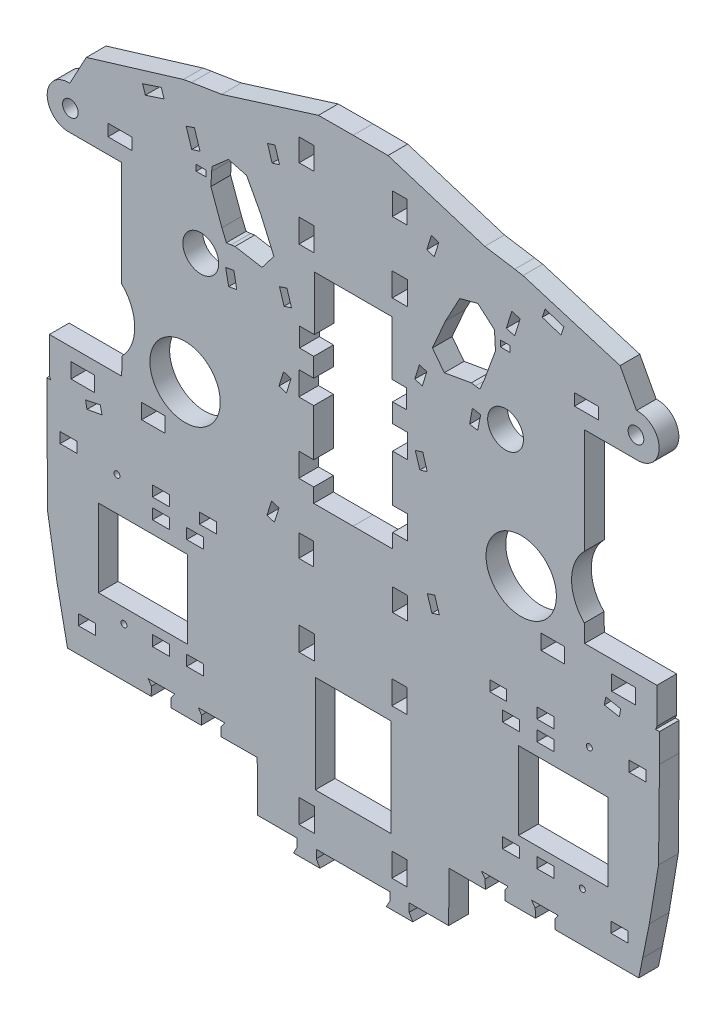
SolidWorks part; units mm, degrees
ref_plane "前视基准面" through (0, 0, 0) normal (0, 0, 1) x (1, 0, 0)
ref_plane "上视基准面" through (0, 0, 0) normal (0, 1, 0) x (1, 0, 0)
ref_plane "右视基准面" through (0, 0, 0) normal (1, 0, 0) x (0, 0, -1)
sketch "草图1" plane through (0, 0, 0) normal (0, 0, 1) x (1, 0, 0)
  line L0 (40.1319, 121.5955) -> (40.4636, 123.1274)
  line L1 (-23.8193, 113.4276) -> (-23.8217, 138.8533)
  line L2 (-75.4253, 72.6956) -> (-75.3783, 72.6832)
  line L3 (-75.4995, 72.7153) -> (-75.4253, 72.6956)
  line L4 (-64.2128, 53.4964) -> (-64.2329, 53.6251)
  line L5 (-69.9682, 79.3438) -> (-69.9274, 79.3967)
  line L6 (-43.5933, 134.7383) -> (-43.5944, 146.0263)
  line L7 (-71.2784, 60.0877) -> (-71.2024, 60.1943)
  line L8 (-76.5092, -117.3385) -> (-76.4093, -117.3385)
  line L9 (-79.6948, -128.8921) -> (-78.1517, -128.025)
  line L10 (-76.5083, -127.1017) -> (-76.4368, -127.1017)
  line L11 (-76.5136, -70.2234) -> (-76.4137, -70.2234)
  line L12 (-76.5127, -79.9866) -> (-76.4128, -79.9866)
  line L13 (-72.2367, -65.4) -> (-68.3488, -65.3726)
  line L14 (45.1325, -17.5397) -> (47.3975, -15.7128)
  line L15 (45.1036, -17.563) -> (45.1325, -17.5397)
  line L16 (21.5769, 33.5708) -> (25.2245, 34.8805)
  line L17 (22.1508, 30.3689) -> (21.5769, 33.5708)
  line L18 (-23.565, -53.6074) -> (-5.931, -53.5258)
  line L19 (46.0726, -27.5191) -> (48.4576, -28.9466)
  line L20 (-19.3181, -41.989) -> (-17.0621, -43.6655)
  line L21 (23.8684, 46.73) -> (23.9576, 46.855)
  line L22 (23.8388, 46.6886) -> (23.8684, 46.73)
  line L23 (27.9944, 34.276) -> (28.1788, 34.2274)
  line L24 (41.1158, -17.8347) -> (45.1036, -17.563)
  line L25 (-19.5903, -41.9817) -> (-19.3181, -41.989)
  line L26 (47.4028, -15.7672) -> (47.3975, -15.7128)
  line L27 (24.5751, -117.3132) -> (24.5716, -79.9772)
  line L28 (78.1472, 49.3388) -> (84.2446, 51.2521)
  line L29 (16.7435, 53.3987) -> (16.7367, 53.4443)
  line L30 (-96.1195, -29.1142) -> (-96.1023, -28.9384)
  line L31 (-69.0029, 33.531) -> (-68.9973, 33.5623)
  line L32 (-51.1518, -3.924) -> (-51.153, 8.006)
  line L33 (-75.5974, 34.2157) -> (-75.5862, 34.2494)
  line L34 (-94.8087, -15.7261) -> (-92.7022, -17.4264)
  line L35 (-93.4236, -27.4919) -> (-89.6822, -27.7541)
  line L36 (-64.3223, 53.462) -> (-64.3152, 53.5103)
  line L37 (-6.1906, 160.47) -> (42.9188, 145.1172)
  line L38 (47.1449, 122.6663) -> (44.8512, 124.5174)
  line L39 (44.8512, 124.5174) -> (40.8238, 124.7905)
  line L40 (-4.0345, 98.9639) -> (-4.0235, 110.8835)
  line L41 (30.217, 115.8395) -> (23.0051, 102.396)
  line L42 (3.6524, 110.864) -> (-4.0235, 110.8835)
  line L43 (17.3013, 127.7476) -> (13.5193, 128.917)
  line L44 (16.3574, 87.2049) -> (22.4022, 79.3476)
  line L45 (3.6414, 98.9339) -> (-4.0345, 98.9639)
  line L46 (-3.9865, 146.0307) -> (3.5762, 146.0856)
  line L47 (19.6115, 135.2186) -> (15.8418, 136.3843)
  line L48 (19.6115, 135.2186) -> (17.3013, 127.7476)
  line L49 (39.4156, 118.2877) -> (39.503, 118.6909)
  line L50 (13.5193, 128.917) -> (15.8418, 136.3843)
  line L51 (39.4156, 118.2877) -> (30.217, 115.8395)
  line L52 (16.3574, 87.2049) -> (23.0051, 102.396)
  line L53 (3.6414, 98.9339) -> (3.6524, 110.864)
  line L54 (3.5771, 134.7408) -> (3.5762, 146.0856)
  line L55 (21.9145, 62.6193) -> (18.2054, 63.9673)
  line L56 (-17.048, 115.4151) -> (-19.5729, 113.5388)
  line L57 (-6.1906, 160.47) -> (-23.8228, 160.5481)
  line L58 (-23.8163, 90.6556) -> (-4.1414, 90.6574)
  line L59 (11.2182, 67.904) -> (7.4362, 69.0735)
  line L60 (3.3412, 53.5022) -> (3.3403, 63.1315)
  line L61 (-19.5729, 113.5388) -> (-23.8193, 113.4276)
  line L62 (18.1801, 63.7969) -> (18.2054, 63.9673)
  line L63 (-17.0496, 137.3564) -> (-17.0513, 150.8079)
  line L64 (7.4362, 69.0735) -> (9.7596, 76.5405)
  line L65 (-17.0463, 101.9645) -> (-19.5098, 103.5819)
  line L66 (-3.9864, 134.7429) -> (3.5771, 134.7408)
  line L67 (-17.0463, 101.9645) -> (-17.048, 115.4151)
  line L68 (-23.8226, 148.8204) -> (-23.8228, 160.5481)
  line L69 (-4.1388, 63.1308) -> (-4.1414, 90.6574)
  line L70 (13.5284, 75.3751) -> (9.7596, 76.5405)
  line L71 (11.2182, 67.904) -> (13.5284, 75.3751)
  line L72 (3.3403, 63.1315) -> (-4.1388, 63.1308)
  line L73 (-63.9249, 87.1964) -> (-70.5783, 102.3878)
  line L74 (-50.9578, 53.4976) -> (-50.9587, 63.1256)
  line L75 (-50.9587, 63.1256) -> (-43.4827, 63.1263)
  line L76 (-43.4827, 63.1263) -> (-43.4852, 90.6543)
  line L77 (-65.7707, 63.9602) -> (-69.4786, 62.6119)
  line L78 (-90.4983, 145.1059) -> (-41.3917, 160.4665)
  line L79 (-51.214, 98.9296) -> (-43.534, 98.9623)
  line L80 (-70.5783, 102.3878) -> (-77.7916, 115.8311)
  line L81 (-41.3917, 160.4665) -> (-23.8228, 160.5481)
  line L82 (-43.4852, 90.6543) -> (-23.8163, 90.6556)
  line L83 (-94.7202, 122.6535) -> (-96.0334, 136.0414)
  line L84 (-93.3364, 134.4217) -> (-89.4053, 134.694)
  line L85 (-51.1544, 146.0816) -> (-51.1533, 134.7376)
  line L86 (-64.8767, 127.7403) -> (-61.0968, 128.9127)
  line L87 (-58.8382, 67.8971) -> (-61.1509, 75.3687)
  line L88 (-77.7916, 115.8311) -> (-86.9918, 118.2783)
  line L89 (-43.534, 98.9623) -> (-43.5471, 110.8823)
  line L90 (-89.4053, 134.694) -> (-90.4983, 145.1059)
  line L91 (-57.3799, 76.537) -> (-61.1509, 75.3687)
  line L92 (-51.1533, 134.7376) -> (-43.5933, 134.7383)
  line L93 (-61.0968, 128.9127) -> (-63.4215, 136.3764)
  line L94 (-57.3799, 76.537) -> (-55.0552, 69.0692)
  line L95 (-64.8767, 127.7403) -> (-67.1894, 135.2121)
  line L96 (-43.5944, 146.0263) -> (-51.1544, 146.0816)
  line L97 (-63.4215, 136.3764) -> (-67.1894, 135.2121)
  line L98 (-51.2271, 110.8576) -> (-51.214, 98.9296)
  line L99 (-43.5471, 110.8823) -> (-51.2271, 110.8576)
  line L100 (-58.8382, 67.8971) -> (-55.0552, 69.0692)
  line L101 (-72.7515, 71.9876) -> (-75.3783, 72.6832)
  line L102 (-71.2024, 60.1943) -> (-69.4786, 62.6119)
  line L103 (-64.0962, 53.4964) -> (-50.9578, 53.4976)
  line L104 (-19.5419, 138.9757) -> (-19.5131, 138.9747)
  line L105 (60.0533, -65.6151) -> (105.3501, -65.6151)
  line L106 (124.7675, -49.2798) -> (124.7675, -43.9386)
  line L107 (106.9126, -119.2515) -> (106.9126, -124.5927)
  line L108 (131.5142, -23.7313) -> (131.5142, -38.1518)
  line L109 (60.0533, -65.6151) -> (60.0533, -105.0597)
  line L110 (105.3501, -105.0597) -> (60.0533, -105.0597)
  line L111 (116.1591, -43.9386) -> (124.7675, -43.9386)
  line L112 (115.5201, -124.5927) -> (106.9126, -124.5927)
  line L113 (32.2419, -129.0028) -> (32.2419, -115.5769)
  line L114 (32.0238, -115.6974) -> (32.2419, -115.5769)
  line L115 (115.5201, -124.5927) -> (115.5201, -119.2515)
  line L116 (131.5142, -23.7313) -> (129.5469, -23.7313)
  line L117 (124.7675, -49.2798) -> (116.1601, -49.2798)
  line L118 (32.2419, -81.8877) -> (32.2419, -68.4618)
  line L119 (28.9553, -117.3934) -> (24.7931, -117.3934)
  line L120 (24.7931, -137.0741) -> (24.7931, -127.1566)
  line L121 (43.2128, -137.1757) -> (24.7931, -137.0741)
  line L122 (43.2128, -137.1757) -> (43.1019, -132.6787)
  line L123 (43.1019, -132.6787) -> (41.2259, -130.1536)
  line L124 (41.2259, -130.1536) -> (54.6773, -130.1531)
  line L125 (53.0588, -132.6165) -> (54.6773, -130.1531)
  line L126 (53.1798, -137.1757) -> (53.0588, -132.6165)
  line L127 (68.6037, -137.1757) -> (53.1798, -137.1757)
  line L128 (68.4928, -132.6787) -> (68.6037, -137.1757)
  line L129 (66.6168, -130.1536) -> (68.4928, -132.6787)
  line L130 (80.0682, -130.1531) -> (66.6168, -130.1536)
  line L131 (78.4498, -132.6165) -> (80.0682, -130.1531)
  line L132 (78.5707, -137.1757) -> (78.4498, -132.6165)
  line L133 (78.5707, -137.1757) -> (121.0052, -137.2023)
  line L134 (123.0125, -127.3697) -> (121.0052, -137.2023)
  line L135 (123.0125, -127.3697) -> (126.3749, -110.7223)
  line L136 (131.0458, -82.5131) -> (126.3749, -110.7223)
  line L137 (131.5142, -38.1518) -> (131.0458, -82.5131)
  line L138 (123.7326, -38.1518) -> (114.1111, -38.1518)
  line L139 (114.1111, -38.1518) -> (113.9902, -33.5926)
  line L140 (115.6087, -31.1292) -> (113.9902, -33.5926)
  line L141 (102.1572, -31.1297) -> (115.6087, -31.1292)
  line L142 (104.0332, -33.6548) -> (102.1572, -31.1297)
  line L143 (104.1441, -38.1518) -> (104.0332, -33.6548)
  line L144 (78.8927, -38.1518) -> (104.1441, -38.1518)
  line L145 (78.7718, -33.5926) -> (78.8927, -38.1518)
  line L146 (66.9388, -31.1297) -> (80.3894, -31.1332)
  line L147 (68.8148, -33.6548) -> (66.9388, -31.1297)
  line L148 (68.9257, -38.1518) -> (68.8148, -33.6548)
  line L149 (28.9553, -70.2783) -> (24.7931, -70.2783)
  line L150 (91.7893, -110.9056) -> (92.3726, -110.7896)
  line L151 (92.9558, -110.9056) -> (92.3726, -110.7896)
  line L152 (93.4502, -111.236) -> (92.9558, -110.9056)
  line L153 (93.7806, -111.7304) -> (93.4502, -111.236)
  line L154 (93.8966, -112.3136) -> (93.7806, -111.7304)
  line L155 (93.7806, -112.8969) -> (93.8966, -112.3136)
  line L156 (93.4502, -113.3913) -> (93.7806, -112.8969)
  line L157 (92.9558, -113.7217) -> (93.4502, -113.3913)
  line L158 (92.3726, -113.8377) -> (92.9558, -113.7217)
  line L159 (91.7893, -113.7217) -> (92.3726, -113.8377)
  line L160 (91.2949, -113.3913) -> (91.7893, -113.7217)
  line L161 (90.9645, -112.8969) -> (91.2949, -113.3913)
  line L162 (90.8485, -112.3136) -> (90.9645, -112.8969)
  line L163 (90.9645, -111.7304) -> (90.8485, -112.3136)
  line L164 (91.2949, -111.236) -> (90.9645, -111.7304)
  line L165 (91.7893, -110.9056) -> (91.2949, -111.236)
  line L166 (116.1591, -43.9386) -> (116.1601, -49.2798)
  line L167 (106.9126, -119.2515) -> (115.5201, -119.2515)
  line L168 (94.5362, -48.9646) -> (94.8665, -49.459)
  line L169 (94.4202, -48.3814) -> (94.5362, -48.9646)
  line L170 (94.5362, -47.7982) -> (94.4202, -48.3814)
  line L171 (94.8665, -47.3037) -> (94.5362, -47.7982)
  line L172 (95.361, -46.9734) -> (94.8665, -47.3037)
  line L173 (95.361, -46.9734) -> (95.9442, -46.8574)
  line L174 (95.9442, -46.8574) -> (96.5274, -46.9734)
  line L175 (96.5274, -46.9734) -> (97.0218, -47.3037)
  line L176 (97.0218, -47.3037) -> (97.3522, -47.7982)
  line L177 (97.4682, -48.3814) -> (97.3522, -47.7982)
  line L178 (97.3522, -48.9646) -> (97.4682, -48.3814)
  line L179 (97.3522, -48.9646) -> (97.0218, -49.459)
  line L180 (97.0218, -49.459) -> (96.5274, -49.7894)
  line L181 (96.5274, -49.7894) -> (95.9442, -49.9054)
  line L182 (95.9442, -49.9054) -> (95.361, -49.7894)
  line L183 (95.361, -49.7894) -> (94.8665, -49.459)
  line L184 (77.9262, -49.2798) -> (77.9262, -43.9386)
  line L185 (77.9262, -49.2798) -> (69.3177, -49.2798)
  line L186 (69.3177, -49.2798) -> (69.3177, -43.9386)
  line L187 (69.3177, -43.9386) -> (77.9262, -43.9386)
  line L188 (54.053, -43.9386) -> (54.053, -49.2798)
  line L189 (45.4446, -49.2798) -> (54.053, -49.2798)
  line L190 (45.4446, -49.2798) -> (45.4446, -43.9386)
  line L191 (45.4446, -43.9386) -> (54.053, -43.9386)
  line L192 (60.5583, -53.9613) -> (60.5583, -59.3025)
  line L193 (51.9499, -59.3025) -> (60.5583, -59.3025)
  line L194 (51.9499, -53.9613) -> (51.9499, -59.3025)
  line L195 (51.9499, -53.9613) -> (60.5583, -53.9613)
  line L196 (77.9262, -59.3025) -> (69.3177, -59.3025)
  line L197 (69.3177, -53.9613) -> (69.3177, -59.3025)
  line L198 (69.3177, -53.9613) -> (77.9262, -53.9613)
  line L199 (51.9513, -114.9842) -> (60.5597, -114.9842)
  line L200 (51.9513, -109.643) -> (51.9513, -114.9842)
  line L201 (60.5597, -109.643) -> (51.9513, -109.643)
  line L202 (60.5597, -114.9842) -> (60.5597, -109.643)
  line L203 (77.9262, -114.9842) -> (77.9262, -109.643)
  line L204 (69.3177, -114.9842) -> (77.9262, -114.9842)
  line L205 (69.3177, -109.643) -> (69.3177, -114.9842)
  line L206 (77.9262, -109.643) -> (69.3177, -109.643)
  line L207 (105.3501, -65.6151) -> (105.3501, -105.0597)
  line L208 (28.849, -80.0414) -> (24.7931, -80.0612)
  line L209 (32.2419, -81.8877) -> (32.0007, -81.7522)
  line L210 (32.0194, -68.5847) -> (32.2419, -68.4618)
  line L211 (28.8818, -127.1566) -> (24.7931, -127.1566)
  line L212 (77.9271, -59.2742) -> (77.9262, -59.3025)
  line L213 (-152.9089, -65.5674) -> (-107.6121, -65.5631)
  line L214 (-172.3284, -43.8927) -> (-172.3279, -49.2339)
  line L215 (-154.4655, -119.2039) -> (-154.465, -124.5451)
  line L216 (-179.076, -23.686) -> (-179.0746, -38.1065)
  line L217 (-107.6084, -105.0078) -> (-107.6121, -65.5631)
  line L218 (-107.6084, -105.0078) -> (-152.9052, -105.012)
  line L219 (-172.3284, -43.8927) -> (-163.72, -43.8919)
  line L220 (-163.0734, -124.5459) -> (-154.465, -124.5451)
  line L221 (-79.7939, -128.9477) -> (-79.7951, -115.5227)
  line L222 (-163.0734, -124.5459) -> (-163.0739, -119.2047)
  line L223 (-179.076, -23.686) -> (-177.1096, -23.6858)
  line L224 (-172.3279, -49.2339) -> (-163.7195, -49.233)
  line L225 (-79.7983, -81.8326) -> (-79.7995, -68.4076)
  line L226 (-72.3461, -117.3222) -> (-72.3496, -80.006)
  line L227 (-72.3443, -137.0189) -> (-72.3452, -127.1014)
  line L228 (-90.764, -137.1222) -> (-72.3443, -137.0189)
  line L229 (-88.7787, -130.0999) -> (-102.2292, -130.1007)
  line L230 (-100.6105, -132.5639) -> (-102.2292, -130.1007)
  line L231 (-100.731, -137.1231) -> (-100.6105, -132.5639)
  line L232 (-116.1549, -137.1246) -> (-100.731, -137.1231)
  line L233 (-127.6201, -130.1031) -> (-114.1696, -130.1023)
  line L234 (-126.0014, -132.5663) -> (-127.6201, -130.1031)
  line L235 (-126.1219, -137.1255) -> (-126.0014, -132.5663)
  line L236 (-64.3466, -46.4962) -> (-89.1328, -38.6309)
  line L237 (-90.582, -38.1713) -> (-90.7877, -38.1058)
  line L238 (-64.3449, -65.3254) -> (-64.3466, -46.4962)
  line L239 (-72.3509, -65.4009) -> (-72.2367, -65.4)
  line L240 (-72.3505, -70.223) -> (-72.3509, -65.4009)
  line L241 (-140.5094, -110.8568) -> (-139.9267, -110.7408)
  line L242 (-141.0038, -111.1872) -> (-140.5094, -110.8568)
  line L243 (-141.3341, -111.6816) -> (-141.0038, -111.1872)
  line L244 (-141.4501, -112.2649) -> (-141.3341, -111.6816)
  line L245 (-141.334, -112.8481) -> (-141.4501, -112.2649)
  line L246 (-141.0036, -113.3425) -> (-141.334, -112.8481)
  line L247 (-140.5092, -113.6728) -> (-141.0036, -113.3425)
  line L248 (-139.9264, -113.7887) -> (-140.5092, -113.6728)
  line L249 (-143.5043, -46.8089) -> (-144.087, -46.9249)
  line L250 (-144.087, -46.9249) -> (-144.5814, -47.2552)
  line L251 (-144.5814, -47.2552) -> (-144.9117, -47.7497)
  line L252 (-145.0277, -48.3329) -> (-144.9117, -47.7497)
  line L253 (-144.9116, -48.9162) -> (-145.0277, -48.3329)
  line L254 (-144.9116, -48.9162) -> (-144.5812, -49.4106)
  line L255 (-144.5812, -49.4106) -> (-144.0868, -49.7409)
  line L256 (-144.0868, -49.7409) -> (-143.504, -49.8567)
  line L257 (-125.4856, -49.2295) -> (-125.4861, -43.8883)
  line L258 (-101.6129, -43.8861) -> (-101.6124, -49.2273)
  line L259 (-93.0049, -49.2265) -> (-101.6124, -49.2273)
  line L260 (-108.1173, -53.9094) -> (-108.1168, -59.2506)
  line L261 (-99.5093, -59.2498) -> (-108.1168, -59.2506)
  line L262 (-125.4851, -53.911) -> (-125.4846, -59.2522)
  line L263 (-99.5055, -114.9316) -> (-108.113, -114.9324)
  line L264 (-108.1135, -109.5912) -> (-99.506, -109.5903)
  line L265 (-108.113, -114.9324) -> (-108.1135, -109.5912)
  line L266 (-125.4794, -114.934) -> (-125.4799, -109.5928)
  line L267 (-116.872, -114.9332) -> (-125.4794, -114.934)
  line L268 (-125.4799, -109.5928) -> (-116.8725, -109.592)
  line L269 (-152.9089, -65.5674) -> (-152.9052, -105.012)
  line L270 (-127.9521, -31.0791) -> (-114.5008, -31.0783)
  line L271 (-126.4538, -38.1016) -> (-126.3333, -33.5425)
  line L272 (-151.7055, -38.1039) -> (-126.4538, -38.1016)
  line L273 (-163.1705, -31.0824) -> (-149.7192, -31.0815)
  line L274 (-161.5517, -33.5457) -> (-163.1705, -31.0824)
  line L275 (-161.6722, -38.1049) -> (-161.5517, -33.5457)
  line L276 (-161.6722, -38.1049) -> (-171.294, -38.1058)
  line L277 (-178.6031, -82.4678) -> (-179.0746, -38.1065)
  line L278 (-173.9295, -110.6765) -> (-178.6031, -82.4678)
  line L279 (-170.5656, -127.3237) -> (-173.9295, -110.6765)
  line L280 (-168.5574, -137.156) -> (-170.5656, -127.3237)
  line L281 (-126.1219, -137.1255) -> (-168.5574, -137.156)
  line L282 (-116.0453, -132.6276) -> (-114.1696, -130.1023)
  line L283 (-116.1549, -137.1246) -> (-116.0453, -132.6276)
  line L284 (-90.6544, -132.6252) -> (-88.7787, -130.0999)
  line L285 (-90.764, -137.1222) -> (-90.6544, -132.6252)
  line L286 (-139.3439, -110.8567) -> (-139.9267, -110.7408)
  line L287 (-138.8495, -111.187) -> (-139.3439, -110.8567)
  line L288 (-138.5191, -111.6814) -> (-138.8495, -111.187)
  line L289 (-138.403, -112.2646) -> (-138.5191, -111.6814)
  line L290 (-138.5189, -112.8478) -> (-138.403, -112.2646)
  line L291 (-138.8493, -113.3423) -> (-138.5189, -112.8478)
  line L292 (-139.3437, -113.6727) -> (-138.8493, -113.3423)
  line L293 (-139.9264, -113.7887) -> (-139.3437, -113.6727)
  line L294 (-116.872, -114.9332) -> (-116.8725, -109.592)
  line L295 (-125.4856, -49.2295) -> (-116.8781, -49.2287)
  line L296 (-125.4861, -43.8883) -> (-116.8786, -43.8875)
  line L297 (-116.8786, -43.8875) -> (-116.8781, -49.2287)
  line L298 (-93.0054, -43.8853) -> (-101.6129, -43.8861)
  line L299 (-93.0049, -49.2265) -> (-93.0054, -43.8853)
  line L300 (-108.1173, -53.9094) -> (-99.5098, -53.9086)
  line L301 (-99.5093, -59.2498) -> (-99.5098, -53.9086)
  line L302 (-163.7195, -49.233) -> (-163.72, -43.8919)
  line L303 (-125.4846, -59.2522) -> (-116.8772, -59.2514)
  line L304 (-125.4851, -53.911) -> (-116.8777, -53.9102)
  line L305 (-116.8772, -59.2514) -> (-116.8777, -53.9102)
  line L306 (-143.504, -49.8567) -> (-142.9213, -49.7408)
  line L307 (-143.5043, -46.8089) -> (-142.9215, -46.9247)
  line L308 (-142.4271, -47.255) -> (-142.9215, -46.9247)
  line L309 (-142.0966, -47.7494) -> (-142.4271, -47.255)
  line L310 (-141.9806, -48.3327) -> (-142.0966, -47.7494)
  line L311 (-142.0965, -48.9159) -> (-141.9806, -48.3327)
  line L312 (-142.4269, -49.4104) -> (-142.0965, -48.9159)
  line L313 (-142.9213, -49.7408) -> (-142.4269, -49.4104)
  line L314 (-163.0739, -119.2047) -> (-154.4655, -119.2039)
  line L315 (-99.5055, -114.9316) -> (-99.506, -109.5903)
  line L316 (3.7406, -27.7949) -> (-3.8354, -27.7976)
  line L317 (-16.7939, -43.8648) -> (-16.7952, -30.4148)
  line L318 (3.735, 31.8031) -> (3.7339, 43.8151)
  line L319 (-3.841, 31.8024) -> (3.735, 31.8031)
  line L320 (-3.841, 31.8024) -> (-3.8388, 7.9804)
  line L321 (3.7372, 8.0131) -> (-3.8388, 7.9804)
  line L322 (3.7383, -3.9169) -> (3.7372, 8.0131)
  line L323 (-3.8376, -3.9396) -> (3.7383, -3.9169)
  line L324 (-3.837, -11.1616) -> (-3.8376, -3.9396)
  line L325 (-23.569, -11.1894) -> (-3.837, -11.1616)
  line L326 (-23.567, -31.9134) -> (-23.569, -11.1894)
  line L327 (23.2536, 4.5529) -> (30.4688, -8.8884)
  line L328 (22.6474, 27.5989) -> (16.6041, 19.7443)
  line L329 (-3.8421, 43.8144) -> (-3.843, 53.4364)
  line L330 (3.7339, 43.8151) -> (-3.8421, 43.8144)
  line L331 (-3.8354, -27.7976) -> (-3.8344, -39.0856)
  line L332 (3.7416, -39.1389) -> (3.7406, -27.7949)
  line L333 (-3.8344, -39.0856) -> (3.7416, -39.1389)
  line L334 (17.5539, -20.7996) -> (13.772, -21.9699)
  line L335 (17.5539, -20.7996) -> (19.8666, -28.2694)
  line L336 (16.0967, -29.4357) -> (19.8666, -28.2694)
  line L337 (13.772, -21.9699) -> (16.0967, -29.4357)
  line L338 (7.6785, 37.8735) -> (10.0031, 30.4057)
  line L339 (11.4603, 39.0438) -> (7.6785, 37.8735)
  line L340 (13.771, 31.5721) -> (11.4603, 39.0438)
  line L341 (10.0031, 30.4057) -> (13.771, 31.5721)
  line L342 (25.3725, 34.9333) -> (25.4267, 34.9531)
  line L343 (22.6474, 27.5989) -> (22.1508, 30.3689)
  line L344 (16.5011, 53.4442) -> (-3.843, 53.4364)
  line L345 (-17.0634, -30.5911) -> (-16.7952, -30.4148)
  line L346 (-16.7939, -43.8648) -> (-17.0621, -43.6655)
  line L347 (48.7107, -29.0987) -> (47.4028, -15.7672)
  line L348 (18.446, 42.9805) -> (18.421, 43.1493)
  line L349 (-54.121, -169.8559) -> (-52.2752, -166.569)
  line L350 (-72.2428, -162.4166) -> (-72.2461, -127.0854)
  line L351 (-51.2429, -155.9829) -> (-43.5661, -156.0025)
  line L352 (-43.5731, -80.2888) -> (-43.5622, -68.3693)
  line L353 (16.787, -65.3179) -> (16.5691, -65.3179)
  line L354 (-72.2514, -70.223) -> (-72.3505, -70.223)
  line L355 (16.5691, -65.3179) -> (16.5674, -46.4874)
  line L356 (-64.2498, -65.3254) -> (-64.2516, -46.4422)
  line L357 (-54.121, -169.8559) -> (-40.6941, -169.8546)
  line L358 (-40.6941, -169.8546) -> (-42.511, -166.5681)
  line L359 (24.5716, -79.9772) -> (28.7339, -79.9768)
  line L360 (-76.4368, -127.1017) -> (-76.4084, -127.0858)
  line L361 (-72.3496, -80.006) -> (-72.2505, -79.9862)
  line L362 (-76.4128, -79.9866) -> (-79.6992, -81.8331)
  line L363 (-42.511, -166.5681) -> (-42.5114, -162.4099)
  line L364 (-6.7803, -162.4066) -> (-5.1763, -162.4064)
  line L365 (24.7931, -70.214) -> (24.5716, -70.214)
  line L366 (-72.247, -117.3222) -> (-72.3461, -117.3222)
  line L367 (-50.3074, -50.7676) -> (-64.2516, -46.4422)
  line L368 (-23.565, -53.375) -> (-23.8392, -53.3751)
  line L369 (-5.1759, -166.5646) -> (-5.1763, -162.4064)
  line L370 (-7.0219, -169.8515) -> (-5.1759, -166.5646)
  line L371 (-79.7005, -68.407) -> (-76.4137, -70.2234)
  line L372 (32.0113, -128.8733) -> (32.0238, -115.6974)
  line L373 (3.5339, -155.9779) -> (-4.2194, -155.9777)
  line L374 (24.577, -127.0764) -> (28.7382, -127.076)
  line L375 (24.7931, -117.3132) -> (24.5751, -117.3132)
  line L376 (-43.5661, -156.0025) -> (-43.5551, -144.0828)
  line L377 (-39.3234, -162.4135) -> (-8.3843, -162.4107)
  line L378 (-42.5114, -162.4099) -> (-40.9055, -162.4097)
  line L379 (3.5268, -144.0477) -> (-4.1562, -144.0792)
  line L380 (32.0007, -81.7522) -> (32.0194, -68.5847)
  line L381 (-51.2389, -68.3392) -> (-51.25, -80.2693)
  line L382 (3.5268, -80.2642) -> (-4.2265, -80.2641)
  line L383 (-72.247, -117.3222) -> (-72.2505, -79.9862)
  line L384 (28.7329, -70.2136) -> (32.0194, -68.3968)
  line L385 (28.7373, -117.3128) -> (32.0238, -115.496)
  line L386 (-43.5551, -144.0828) -> (-51.2319, -144.0528)
  line L387 (-51.25, -80.2693) -> (-43.5731, -80.2888)
  line L388 (-5.7866, -53.3734) -> (16.5664, -46.4347)
  line L389 (-51.2319, -144.0528) -> (-51.2429, -155.9829)
  line L390 (-52.2752, -166.569) -> (-52.2755, -162.4107)
  line L391 (-43.5622, -68.3693) -> (-51.2389, -68.3392)
  line L392 (-4.2265, -80.2641) -> (-4.1623, -68.3656)
  line L393 (24.5793, -162.4076) -> (24.577, -127.0764)
  line L394 (-4.2194, -155.9777) -> (-4.1562, -144.0792)
  line L395 (3.5268, -80.2642) -> (3.5137, -68.3341)
  line L396 (4.5882, -166.5637) -> (4.5869, -162.4015)
  line L397 (6.4052, -169.8502) -> (4.5882, -166.5637)
  line L398 (-7.0219, -169.8515) -> (6.4052, -169.8502)
  line L399 (-64.2498, -65.3254) -> (-64.3449, -65.3254)
  line L400 (24.5716, -70.214) -> (24.5703, -65.4547)
  line L401 (-4.1623, -68.3656) -> (3.5137, -68.3341)
  line L402 (-42.9186, -136.5506) -> (-42.8629, -87.0104)
  line L403 (-4.7404, -136.631) -> (-42.9186, -136.5506)
  line L404 (-4.6848, -87.1346) -> (-42.8629, -87.0104)
  line L405 (-79.6961, -115.5062) -> (-76.4093, -117.3385)
  line L406 (-4.7404, -136.631) -> (-4.6848, -87.1346)
  line L407 (16.6681, 19.725) -> (23.205, 4.723)
  line L408 (130.2103, -4.0184) -> (93.5623, -4.0218)
  line L409 (78.8988, 13.0077) -> (79.2419, 9.5268)
  line L410 (76.2339, 19.4395) -> (77.883, 16.3548)
  line L411 (76.2358, -0.3865) -> (74.017, -3.0906)
  line L412 (80.3678, 57.3955) -> (81.8198, 53.1379)
  line L413 (93.5411, 61.5734) -> (93.5484, 36.5375)
  line L414 (86.8457, 20.7302) -> (87.2756, 16.3691)
  line L415 (43.9002, 6.0425) -> (44.9158, 2.6954)
  line L416 (46.0726, -27.5191) -> (42.116, -27.7881)
  line L417 (90.611, 33.1498) -> (93.5484, 36.5375)
  line L418 (88.5456, 29.2849) -> (90.611, 33.1498)
  line L419 (81.8198, 53.1379) -> (84.3658, 51.2901)
  line L420 (90.6142, 8.3112) -> (93.3945, 4.924)
  line L421 (79.2419, 9.5268) -> (78.8994, 6.0458)
  line L422 (44.9158, 2.6954) -> (46.565, -0.3892)
  line L423 (64.8784, 27.0255) -> (68.2256, 26.0105)
  line L424 (68.2256, 26.0105) -> (71.3106, 24.3619)
  line L425 (130.213, -22.0723) -> (130.2103, -4.0184)
  line L426 (44.9137, 16.3518) -> (46.5622, 19.4367)
  line L427 (43.8986, 13.0045) -> (44.9137, 16.3518)
  line L428 (43.5561, 9.5235) -> (43.8986, 13.0045)
  line L429 (43.9002, 6.0425) -> (43.5561, 9.5235)
  line L430 (48.7833, -3.0929) -> (46.565, -0.3892)
  line L431 (51.4873, -5.3116) -> (48.7833, -3.0929)
  line L432 (54.5723, -6.9602) -> (51.4873, -5.3116)
  line L433 (57.9196, -7.9753) -> (54.5723, -6.9602)
  line L434 (61.4007, -8.3178) -> (57.9196, -7.9753)
  line L435 (64.8816, -7.9746) -> (61.4007, -8.3178)
  line L436 (68.2287, -6.959) -> (64.8816, -7.9746)
  line L437 (71.3133, -5.3098) -> (68.2287, -6.959)
  line L438 (74.017, -3.0906) -> (71.3133, -5.3098)
  line L439 (77.8843, 2.6985) -> (76.2358, -0.3865)
  line L440 (78.8994, 6.0458) -> (77.8843, 2.6985)
  line L441 (42.116, -27.7881) -> (43.2272, -38.1593)
  line L442 (47.4322, -15.7436) -> (48.7384, -29.1177)
  line L443 (41.1158, -17.8347) -> (45.1282, -17.5915)
  line L444 (39.7064, -11.3609) -> (41.1158, -17.8347)
  line L445 (22.788, 27.638) -> (16.6681, 19.725)
  line L446 (21.401, 33.5825) -> (25.2529, 34.9651)
  line L447 (23.7689, 46.8973) -> (21.9902, 44.4136)
  line L448 (74.0147, 22.1432) -> (76.2339, 19.4395)
  line L449 (71.3106, 24.3619) -> (74.0147, 22.1432)
  line L450 (61.3973, 27.368) -> (64.8784, 27.0255)
  line L451 (57.9164, 27.0249) -> (61.3973, 27.368)
  line L452 (54.5693, 26.0092) -> (57.9164, 27.0249)
  line L453 (51.4846, 24.3601) -> (54.5693, 26.0092)
  line L454 (48.7809, 22.1408) -> (51.4846, 24.3601)
  line L455 (46.5622, 19.4367) -> (48.7809, 22.1408)
  line L456 (71.4698, -18.1114) -> (71.4893, -10.4346)
  line L457 (83.3894, -18.1224) -> (71.4698, -18.1114)
  line L458 (83.4194, -10.4456) -> (83.3894, -18.1224)
  line L459 (71.4893, -10.4346) -> (83.4194, -10.4456)
  line L460 (119.235, -18.1191) -> (107.3154, -18.1081)
  line L461 (119.265, -10.4423) -> (119.235, -18.1191)
  line L462 (107.3349, -10.4312) -> (119.265, -10.4423)
  line L463 (107.3154, -18.1081) -> (107.3349, -10.4312)
  line L464 (111.8505, -23.5622) -> (111.1537, -27.3996)
  line L465 (104.3599, -22.0472) -> (111.8505, -23.5622)
  line L466 (103.5368, -26.0134) -> (104.3599, -22.0472)
  line L467 (111.1537, -27.3996) -> (103.5368, -26.0134)
  line L468 (47.4322, -15.7436) -> (47.4028, -15.7672)
  line L469 (21.9902, 44.4136) -> (18.421, 43.1493)
  line L470 (88.5456, 29.2849) -> (87.2748, 25.0912)
  line L471 (87.2756, 16.3691) -> (88.5481, 12.1757)
  line L472 (87.2748, 25.0912) -> (86.8457, 20.7302)
  line L473 (88.5481, 12.1757) -> (90.6142, 8.3112)
  line L474 (93.5623, -4.0218) -> (93.3945, 4.924)
  line L475 (-92.3865, -17.5865) -> (-92.5136, -17.5779)
  line L476 (-88.4865, -17.8495) -> (-87.0791, -11.3473)
  line L477 (-64.9634, -20.8076) -> (-67.2726, -28.2775)
  line L478 (-90.582, -38.1713) -> (-89.4896, -27.7676)
  line L479 (-92.5136, -17.5779) -> (-92.5611, -17.5395)
  line L480 (-43.5706, -39.0913) -> (-43.5716, -27.8033)
  line L481 (-43.5716, -27.8033) -> (-51.1496, -27.8)
  line L482 (-64.3152, 53.4368) -> (-43.5792, 53.4327)
  line L483 (-69.5774, 44.3203) -> (-71.3776, 46.8461)
  line L484 (-70.6686, 4.5442) -> (-64.02, 19.7348)
  line L485 (-51.1518, -3.924) -> (-43.5738, -3.9433)
  line L486 (-64.02, 19.7348) -> (-70.0668, 27.5902)
  line L487 (-43.575, 7.9767) -> (-51.153, 8.006)
  line L488 (-61.1822, -21.9769) -> (-64.9634, -20.8076)
  line L489 (-63.5054, -29.4429) -> (-67.2726, -28.2775)
  line L490 (-51.1496, -27.8) -> (-51.1486, -39.146)
  line L491 (-69.5774, 44.3203) -> (-65.8682, 42.9726)
  line L492 (-87.0791, -11.3473) -> (-77.8794, -8.8985)
  line L493 (-63.5054, -29.4429) -> (-61.1822, -21.9769)
  line L494 (-43.5706, -39.0913) -> (-51.1486, -39.146)
  line L495 (-77.8794, -8.8985) -> (-70.6686, 4.5442)
  line L496 (-43.5783, 43.8087) -> (-51.1563, 43.808)
  line L497 (-51.1552, 31.798) -> (-43.5772, 31.7987)
  line L498 (-43.5738, -3.9433) -> (-43.5732, -11.1673)
  line L499 (-55.0977, 37.8676) -> (-58.8818, 39.0373)
  line L500 (-57.421, 30.3997) -> (-61.1902, 31.5651)
  line L501 (-43.575, 7.9767) -> (-43.5772, 31.7987)
  line L502 (-23.8403, -41.8795) -> (-23.5661, -41.8794)
  line L503 (-43.5792, 53.4327) -> (-43.5783, 43.8087)
  line L504 (-51.1563, 43.808) -> (-51.1552, 31.798)
  line L505 (-61.1902, 31.5651) -> (-58.8818, 39.0373)
  line L506 (-23.8422, -11.1895) -> (-43.5732, -11.1673)
  line L507 (-57.421, 30.3997) -> (-55.0977, 37.8676)
  line L508 (-19.6532, -32.0331) -> (-17.0634, -30.4148)
  line L509 (-17.0621, -43.6655) -> (-17.0634, -30.5911)
  line L510 (-23.8392, -53.6075) -> (-41.4732, -53.5291)
  line L511 (-23.8392, -53.3751) -> (-23.8403, -41.8795)
  line L512 (-23.8412, -31.9135) -> (-23.8422, -11.1895)
  line L513 (-17.0621, -43.8668) -> (-19.5903, -41.9817)
  line L514 (-131.9439, 51.3435) -> (-131.8406, 51.3115)
  line L515 (-119.1088, 47.3187) -> (-119.9162, 50.1536)
  line L516 (-64.2403, 19.791) -> (-70.7744, 4.7878)
  line L517 (-141.1301, -3.9702) -> (-177.7771, -3.9736)
  line L518 (-75.5834, 34.2976) -> (-72.8279, 35.0294)
  line L519 (-126.8113, 9.5811) -> (-126.4687, 13.0621)
  line L520 (-125.4537, 16.4094) -> (-123.8051, 19.4944)
  line L521 (-119.9162, 50.1536) -> (-118.4368, 54.4677)
  line L522 (-121.584, -3.0353) -> (-123.8033, -0.3316)
  line L523 (-127.947, 57.4495) -> (-129.3982, 53.1918)
  line L524 (-141.1228, 36.5892) -> (-141.1362, 61.6299)
  line L525 (-97.4406, 47.8963) -> (-91.5033, 49.2302)
  line L526 (-133.9369, 59.3276) -> (-141.1362, 61.6299)
  line L527 (-134.8462, 16.4219) -> (-134.4171, 20.783)
  line L528 (-92.4839, 2.7561) -> (-91.4689, 6.1034)
  line L529 (-70.3608, 27.7028) -> (-69.0029, 33.531)
  line L530 (-138.1856, 33.202) -> (-141.1228, 36.5892)
  line L531 (-136.1196, 29.3374) -> (-138.1856, 33.202)
  line L532 (-129.3982, 53.1918) -> (-131.9439, 51.3435)
  line L533 (-140.963, 4.9756) -> (-138.1833, 8.3634)
  line L534 (-126.4687, 13.0621) -> (-125.4537, 16.4094)
  line L535 (-126.4681, 6.1001) -> (-126.8113, 9.5811)
  line L536 (-94.1325, -0.3288) -> (-92.4839, 2.7561)
  line L537 (-115.798, 26.0668) -> (-112.451, 27.0825)
  line L538 (-118.8827, 24.4177) -> (-115.798, 26.0668)
  line L539 (-177.7771, -3.9736) -> (-177.7764, -22.0275)
  line L540 (-92.4852, 16.4125) -> (-94.1343, 19.4971)
  line L541 (-91.4695, 13.0654) -> (-92.4852, 16.4125)
  line L542 (-91.1263, 9.5845) -> (-91.4695, 13.0654)
  line L543 (-91.4689, 6.1034) -> (-91.1263, 9.5845)
  line L544 (-96.3512, -3.0329) -> (-94.1325, -0.3288)
  line L545 (-99.0548, -5.2522) -> (-96.3512, -3.0329)
  line L546 (-102.1395, -6.9013) -> (-99.0548, -5.2522)
  line L547 (-105.4866, -7.917) -> (-102.1395, -6.9013)
  line L548 (-108.9676, -8.2602) -> (-105.4866, -7.917)
  line L549 (-112.4486, -7.9177) -> (-108.9676, -8.2602)
  line L550 (-115.7959, -6.9026) -> (-112.4486, -7.9177)
  line L551 (-118.8809, -5.254) -> (-115.7959, -6.9026)
  line L552 (-121.584, -3.0353) -> (-118.8809, -5.254)
  line L553 (-125.4533, 2.753) -> (-123.8033, -0.3316)
  line L554 (-126.4681, 6.1001) -> (-125.4533, 2.753)
  line L555 (-94.9977, -15.6834) -> (-96.3015, -29.0578)
  line L556 (-87.2727, -11.2992) -> (-88.6767, -17.7959)
  line L557 (-78.0587, -8.8399) -> (-87.2727, -11.2992)
  line L558 (-70.7744, 4.7878) -> (-78.0587, -8.8399)
  line L559 (-70.3608, 27.7028) -> (-64.2403, 19.791)
  line L560 (-68.9758, 33.6476) -> (-72.8279, 35.0294)
  line L561 (-71.3462, 46.962) -> (-69.567, 44.4786)
  line L562 (-65.8442, 43.1607) -> (-69.567, 44.4786)
  line L563 (-121.5873, 22.1984) -> (-123.8051, 19.4944)
  line L564 (-118.8827, 24.4177) -> (-121.5873, 22.1984)
  line L565 (-108.9709, 27.4257) -> (-112.451, 27.0825)
  line L566 (-105.49, 27.0831) -> (-108.9709, 27.4257)
  line L567 (-102.1426, 26.0681) -> (-105.49, 27.0831)
  line L568 (-99.0577, 24.4195) -> (-102.1426, 26.0681)
  line L569 (-96.3536, 22.2008) -> (-99.0577, 24.4195)
  line L570 (-94.1343, 19.4971) -> (-96.3536, 22.2008)
  line L571 (-119.0349, -18.0557) -> (-119.0558, -10.3788)
  line L572 (-130.9545, -18.0689) -> (-119.0349, -18.0557)
  line L573 (-130.9859, -10.3921) -> (-130.9545, -18.0689)
  line L574 (-119.0558, -10.3788) -> (-130.9859, -10.3921)
  line L575 (-166.8001, -18.0722) -> (-154.8805, -18.059)
  line L576 (-166.8315, -10.3954) -> (-166.8001, -18.0722)
  line L577 (-154.9014, -10.3822) -> (-166.8315, -10.3954)
  line L578 (-154.8805, -18.059) -> (-154.9014, -10.3822)
  line L579 (-159.4146, -23.514) -> (-158.7171, -27.3513)
  line L580 (-151.9243, -21.9976) -> (-159.4146, -23.514)
  line L581 (-151.1004, -25.9636) -> (-151.9243, -21.9976)
  line L582 (-158.7171, -27.3513) -> (-151.1004, -25.9636)
  line L583 (-134.8471, 25.1441) -> (-136.1196, 29.3374)
  line L584 (-136.1179, 12.2283) -> (-134.8462, 16.4219)
  line L585 (-134.4171, 20.783) -> (-134.8471, 25.1441)
  line L586 (-138.1833, 8.3634) -> (-136.1179, 12.2283)
  line L587 (-90.7877, -38.1058) -> (-89.6822, -27.7541)
  line L588 (-65.8442, 43.1607) -> (-64.3223, 53.462)
  line L589 (-141.1301, -3.9702) -> (-140.963, 4.9756)
  line L590 (-136.0131, 103.6834) -> (-136.0131, 97.7273)
  line L591 (-136.0131, 103.6834) -> (-148.0991, 103.6834)
  line L592 (-136.0131, 97.7273) -> (-148.0991, 97.7273)
  line L593 (-148.0991, 103.6834) -> (-148.0991, 97.7273)
  line L594 (-170.421, 98.3454) -> (-170.8125, 99.0211)
  line L595 (-169.9053, 97.7592) -> (-170.421, 98.3454)
  line L596 (-169.285, 97.2847) -> (-169.9053, 97.7592)
  line L597 (-168.5842, 96.9405) -> (-169.285, 97.2847)
  line L598 (-167.8296, 96.7395) -> (-168.5842, 96.9405)
  line L599 (-167.0503, 96.6897) -> (-167.8296, 96.7395)
  line L600 (-167.0503, 96.6897) -> (-166.2763, 96.7928)
  line L601 (-165.5373, 97.0449) -> (-166.2763, 96.7928)
  line L602 (-164.8616, 97.4364) -> (-165.5373, 97.0449)
  line L603 (-164.2753, 97.9522) -> (-164.8616, 97.4364)
  line L604 (-163.801, 98.5724) -> (-164.2753, 97.9522)
  line L605 (-163.4567, 99.2733) -> (-163.801, 98.5724)
  line L606 (-163.2558, 100.0278) -> (-163.4567, 99.2733)
  line L607 (-163.2059, 100.8072) -> (-163.2558, 100.0278)
  line L608 (-163.309, 101.5812) -> (-163.2059, 100.8072)
  line L609 (-163.5611, 102.3202) -> (-163.309, 101.5812)
  line L610 (-163.9526, 102.9958) -> (-163.5611, 102.3202)
  line L611 (-164.4684, 103.5821) -> (-163.9526, 102.9958)
  line L612 (-165.0887, 104.0565) -> (-164.4684, 103.5821)
  line L613 (-165.0887, 104.0565) -> (-165.7895, 104.4007)
  line L614 (-165.7895, 104.4007) -> (-166.5441, 104.6017)
  line L615 (-167.3233, 104.6516) -> (-166.5441, 104.6017)
  line L616 (-168.0973, 104.5484) -> (-167.3233, 104.6516)
  line L617 (-168.8364, 104.2963) -> (-168.0973, 104.5484)
  line L618 (-169.512, 103.9048) -> (-168.8364, 104.2963)
  line L619 (-170.0983, 103.389) -> (-169.512, 103.9048)
  line L620 (-170.5726, 102.7688) -> (-170.0983, 103.389)
  line L621 (-170.5726, 102.7688) -> (-170.9169, 102.068)
  line L622 (-171.1179, 101.3134) -> (-170.9169, 102.068)
  line L623 (-171.1179, 101.3134) -> (-171.1678, 100.5341)
  line L624 (-171.0646, 99.7601) -> (-171.1678, 100.5341)
  line L625 (-170.8125, 99.0211) -> (-171.0646, 99.7601)
  line L626 (-159.1194, 127.0927) -> (-167.4739, 111.5369)
  line L627 (-90.3467, 86.6639) -> (-95.9222, 101.9605)
  line L628 (-88.0559, 81.2196) -> (-90.3467, 86.6639)
  line L629 (-87.8132, 81.1989) -> (-88.0559, 81.2196)
  line L630 (-91.4305, 49.1947) -> (-97.4106, 47.8487)
  line L631 (-69.9274, 79.3967) -> (-83.682, 81.7872)
  line L632 (-81.4974, 50.8553) -> (-72.6641, 52.196)
  line L633 (-86.616, 49.9996) -> (-81.4974, 50.8553)
  line L634 (-95.9222, 101.9605) -> (-95.5582, 108.7325)
  line L635 (-109.8711, 142.0316) -> (-159.1194, 127.0927)
  line L636 (-105.7554, 142.7539) -> (-109.8711, 142.0316)
  line L637 (-65.626, 63.912) -> (-64.0962, 53.4964)
  line L638 (-65.7565, 63.8643) -> (-69.3296, 62.5569)
  line L639 (-69.3296, 62.5569) -> (-71.1297, 59.9769)
  line L640 (-71.1297, 59.9769) -> (-71.2024, 60.1943)
  line L641 (-75.3783, 72.6832) -> (-75.3953, 72.734)
  line L642 (-68.7573, 73.3742) -> (-72.5456, 71.9801)
  line L643 (-69.9274, 79.3967) -> (-68.7573, 73.3742)
  line L644 (-92.4612, 124.4669) -> (-94.7237, 122.6179)
  line L645 (-95.3217, 111.0921) -> (-87.0948, 118.7537)
  line L646 (-88.0402, 123.1162) -> (-88.4269, 124.7573)
  line L647 (-90.5135, 145.1783) -> (-105.7554, 142.7539)
  line L648 (-84.2503, 70.9817) -> (-88.4312, 70.1869)
  line L649 (-95.5582, 108.7325) -> (-95.3217, 111.0921)
  line L650 (-130.8714, 129.817) -> (-121.1553, 132.9876)
  line L651 (-130.8714, 129.817) -> (-129.1657, 125.4625)
  line L652 (-119.6531, 128.5715) -> (-129.1657, 125.4625)
  line L653 (-121.1553, 132.9876) -> (-119.6531, 128.5715)
  line L654 (-168.3725, 89.9094) -> (-174.4245, 92.4027)
  line L655 (-174.4245, 92.4027) -> (-177.4827, 96.2383)
  line L656 (-177.4827, 96.2383) -> (-178.9482, 100.7064)
  line L657 (-177.7117, 104.9364) -> (-178.9482, 100.7064)
  line L658 (-88.4312, 70.1869) -> (-86.9116, 62.5127)
  line L659 (-87.8132, 81.1989) -> (-85.7414, 81.4573)
  line L660 (-85.7414, 81.4573) -> (-83.682, 81.7872)
  line L661 (-86.9116, 62.5127) -> (-88.4664, 70.1884)
  line L662 (-84.2068, 70.9912) -> (-82.8235, 63.2355)
  line L663 (-84.2503, 70.9817) -> (-82.8235, 63.2355)
  line L664 (-84.2068, 70.9912) -> (-84.2503, 70.9817)
  line L665 (-88.4312, 70.1869) -> (-88.4664, 70.1884)
  line L666 (-104.2625, 123.6525) -> (-101.4531, 114.7084)
  line L667 (-105.6716, 113.4239) -> (-108.4297, 122.2042)
  line L668 (-105.6716, 113.4239) -> (-101.4531, 114.7084)
  line L669 (-108.4297, 122.2042) -> (-104.2625, 123.6525)
  line L670 (-103.3813, 107.9967) -> (-98.4012, 108.0138)
  line L671 (-98.4012, 108.0138) -> (-98.3848, 104.9458)
  line L672 (-103.3694, 104.9599) -> (-103.3813, 107.9967)
  line L673 (-98.3848, 104.9458) -> (-103.3694, 104.9599)
  line L674 (-177.7117, 104.9364) -> (-174.1177, 109.3821)
  line L675 (-174.1177, 109.3821) -> (-167.4739, 111.5369)
  line L676 (-109.3258, 66.3079) -> (-109.9013, 67.9947)
  line L677 (-109.9013, 67.9947) -> (-110.1367, 69.7614)
  line L678 (-110.0228, 71.54) -> (-110.1367, 69.7614)
  line L679 (-110.0228, 71.54) -> (-109.5642, 73.2623)
  line L680 (-108.7783, 74.862) -> (-109.5642, 73.2623)
  line L681 (-107.6956, 76.2777) -> (-108.7783, 74.862)
  line L682 (-107.6956, 76.2777) -> (-106.3575, 77.4549)
  line L683 (-106.3575, 77.4549) -> (-104.8153, 78.3485)
  line L684 (-103.1285, 78.9239) -> (-104.8153, 78.3485)
  line L685 (-103.1285, 78.9239) -> (-101.3618, 79.1594)
  line L686 (-99.5832, 79.0456) -> (-101.3618, 79.1594)
  line L687 (-96.2613, 77.801) -> (-97.861, 78.5868)
  line L688 (-96.2613, 77.801) -> (-94.8455, 76.7184)
  line L689 (-94.8455, 76.7184) -> (-93.6684, 75.3801)
  line L690 (-93.6684, 75.3801) -> (-92.7748, 73.838)
  line L691 (-92.7748, 73.838) -> (-92.1993, 72.1512)
  line L692 (-92.1993, 72.1512) -> (-91.9639, 70.3846)
  line L693 (-91.9639, 70.3846) -> (-92.0778, 68.6058)
  line L694 (-92.0778, 68.6058) -> (-92.5364, 66.8836)
  line L695 (-92.5364, 66.8836) -> (-93.3221, 65.2839)
  line L696 (-93.3221, 65.2839) -> (-94.4049, 63.8682)
  line L697 (-94.4049, 63.8682) -> (-95.7431, 62.691)
  line L698 (-95.7431, 62.691) -> (-97.2852, 61.7975)
  line L699 (-97.2852, 61.7975) -> (-98.972, 61.2219)
  line L700 (-100.7388, 60.9866) -> (-98.972, 61.2219)
  line L701 (-100.7388, 60.9866) -> (-102.5174, 61.1004)
  line L702 (-102.5174, 61.1004) -> (-104.2397, 61.559)
  line L703 (-104.2397, 61.559) -> (-105.8394, 62.3448)
  line L704 (-105.8394, 62.3448) -> (-107.2551, 63.4276)
  line L705 (-107.2551, 63.4276) -> (-108.4322, 64.7658)
  line L706 (-108.4322, 64.7658) -> (-109.3258, 66.3079)
  line L707 (-127.947, 57.4495) -> (-127.8622, 57.3995)
  line L708 (-129.3262, 53.1342) -> (-127.8622, 57.3995)
  line L709 (-129.3262, 53.1342) -> (-131.8406, 51.3115)
  line L710 (-118.373, 54.4104) -> (-119.8537, 50.0958)
  line L711 (88.4194, 97.6662) -> (88.4194, 103.6223)
  line L712 (88.4194, 103.6223) -> (100.5054, 103.6223)
  line L713 (100.5054, 97.6662) -> (88.4194, 97.6662)
  line L714 (100.5054, 103.6223) -> (100.5054, 97.6662)
  line L715 (123.2189, 98.96) -> (122.8274, 98.2844)
  line L716 (122.8274, 98.2844) -> (122.3116, 97.6981)
  line L717 (122.3116, 97.6981) -> (121.6914, 97.2237)
  line L718 (121.6914, 97.2237) -> (120.9905, 96.8794)
  line L719 (120.9905, 96.8794) -> (120.2359, 96.6785)
  line L720 (120.2359, 96.6785) -> (119.4567, 96.6286)
  line L721 (119.4567, 96.6286) -> (118.6826, 96.7317)
  line L722 (118.6826, 96.7317) -> (117.9436, 96.9839)
  line L723 (117.9436, 96.9839) -> (117.268, 97.3754)
  line L724 (117.268, 97.3754) -> (116.6817, 97.8911)
  line L725 (116.6817, 97.8911) -> (116.2073, 98.5114)
  line L726 (116.2073, 98.5114) -> (115.8631, 99.2122)
  line L727 (115.8631, 99.2122) -> (115.6621, 99.9668)
  line L728 (115.6621, 99.9668) -> (115.6122, 100.7461)
  line L729 (115.6122, 100.7461) -> (115.7154, 101.5201)
  line L730 (115.7154, 101.5201) -> (115.9675, 102.2591)
  line L731 (115.9675, 102.2591) -> (116.359, 102.9347)
  line L732 (116.359, 102.9347) -> (116.8747, 103.521)
  line L733 (116.8747, 103.521) -> (117.495, 103.9954)
  line L734 (117.495, 103.9954) -> (118.1959, 104.3397)
  line L735 (118.1959, 104.3397) -> (118.9504, 104.5407)
  line L736 (118.9504, 104.5407) -> (119.7296, 104.5905)
  line L737 (119.7296, 104.5905) -> (120.5037, 104.4874)
  line L738 (120.5037, 104.4874) -> (121.2427, 104.2352)
  line L739 (121.2427, 104.2352) -> (121.9184, 103.8437)
  line L740 (121.9184, 103.8437) -> (122.5047, 103.328)
  line L741 (122.979, 102.7077) -> (122.5047, 103.328)
  line L742 (122.979, 102.7077) -> (123.3233, 102.0069)
  line L743 (123.3233, 102.0069) -> (123.5242, 101.2523)
  line L744 (123.5242, 101.2523) -> (123.5741, 100.4731)
  line L745 (123.5741, 100.4731) -> (123.471, 99.699)
  line L746 (123.471, 99.699) -> (123.2189, 98.96)
  line L747 (119.8803, 111.4759) -> (111.5258, 127.0316)
  line L748 (48.3285, 101.8994) -> (42.7531, 86.6028)
  line L749 (42.7531, 86.6028) -> (40.4623, 81.1585)
  line L750 (40.4623, 81.1585) -> (40.2195, 81.1378)
  line L751 (43.8369, 49.1336) -> (49.8169, 47.7876)
  line L752 (36.0884, 81.7262) -> (22.4022, 79.3476)
  line L753 (47.9646, 108.6714) -> (48.3285, 101.8994)
  line L754 (111.5258, 127.0316) -> (62.2774, 141.9705)
  line L755 (62.2774, 141.9705) -> (58.1618, 142.6928)
  line L756 (18.1801, 63.7969) -> (21.736, 62.4958)
  line L757 (21.736, 62.4958) -> (23.536, 59.9159)
  line L758 (23.536, 59.9159) -> (23.6342, 60.21)
  line L759 (21.1636, 73.3131) -> (24.9519, 71.919)
  line L760 (22.3116, 79.3318) -> (21.1636, 73.3131)
  line L761 (41.8117, 134.6328) -> (45.7213, 134.3604)
  line L762 (47.13, 122.5568) -> (47.1449, 122.6663)
  line L763 (44.8675, 124.4058) -> (47.13, 122.5568)
  line L764 (44.8675, 124.4058) -> (40.8332, 124.6963)
  line L765 (58.1618, 142.6928) -> (42.9188, 145.1172)
  line L766 (36.6566, 70.9206) -> (40.8375, 70.1258)
  line L767 (47.728, 111.031) -> (47.9646, 108.6714)
  line L768 (83.2777, 129.756) -> (73.5616, 132.9265)
  line L769 (83.2777, 129.756) -> (81.5721, 125.4014)
  line L770 (81.5721, 125.4014) -> (72.0594, 128.5104)
  line L771 (72.0594, 128.5104) -> (73.5616, 132.9265)
  line L772 (120.7788, 89.8484) -> (126.8309, 92.3416)
  line L773 (126.8309, 92.3416) -> (129.889, 96.1772)
  line L774 (129.889, 96.1772) -> (131.3545, 100.6453)
  line L775 (130.118, 104.8753) -> (131.3545, 100.6453)
  line L776 (40.8375, 70.1258) -> (39.3179, 62.4516)
  line L777 (38.1477, 81.3962) -> (36.0884, 81.7262)
  line L778 (40.2195, 81.1378) -> (38.1477, 81.3962)
  line L779 (39.3179, 62.4516) -> (40.8727, 70.1273)
  line L780 (36.6132, 70.9301) -> (35.2298, 63.1744)
  line L781 (36.6566, 70.9206) -> (35.2298, 63.1744)
  line L782 (36.6132, 70.9301) -> (36.6566, 70.9206)
  line L783 (40.8375, 70.1258) -> (40.8727, 70.1273)
  line L784 (53.8594, 114.6473) -> (56.6689, 123.5914)
  line L785 (60.836, 122.1431) -> (58.078, 113.3628)
  line L786 (58.078, 113.3628) -> (53.8594, 114.6473)
  line L787 (56.6689, 123.5914) -> (60.836, 122.1431)
  line L788 (55.7876, 107.9357) -> (50.8075, 107.9527)
  line L789 (50.8075, 107.9527) -> (50.7911, 104.8848)
  line L790 (55.7757, 104.8988) -> (55.7876, 107.9357)
  line L791 (55.7757, 104.8988) -> (50.7911, 104.8848)
  line L792 (130.118, 104.8753) -> (126.5241, 109.321)
  line L793 (126.5241, 109.321) -> (119.8803, 111.4759)
  line L794 (62.3076, 67.9336) -> (61.7322, 66.2468)
  line L795 (62.543, 69.7003) -> (62.3076, 67.9336)
  line L796 (62.4291, 71.4789) -> (62.543, 69.7003)
  line L797 (61.9705, 73.2013) -> (62.4291, 71.4789)
  line L798 (61.1847, 74.8009) -> (61.9705, 73.2013)
  line L799 (60.1019, 76.2166) -> (61.1847, 74.8009)
  line L800 (58.7639, 77.3938) -> (60.1019, 76.2166)
  line L801 (57.2216, 78.2874) -> (58.7639, 77.3938)
  line L802 (55.5348, 78.8629) -> (57.2216, 78.2874)
  line L803 (53.7681, 79.0983) -> (55.5348, 78.8629)
  line L804 (51.9895, 78.9845) -> (53.7681, 79.0983)
  line L805 (48.6676, 77.74) -> (50.2673, 78.5257)
  line L806 (47.2518, 76.6573) -> (48.6676, 77.74)
  line L807 (46.0747, 75.319) -> (47.2518, 76.6573)
  line L808 (45.1811, 73.777) -> (46.0747, 75.319)
  line L809 (44.6057, 72.0901) -> (45.1811, 73.777)
  line L810 (44.3702, 70.3235) -> (44.6057, 72.0901)
  line L811 (44.4841, 68.5448) -> (44.3702, 70.3235)
  line L812 (44.9428, 66.8225) -> (44.4841, 68.5448)
  line L813 (45.7285, 65.2229) -> (44.9428, 66.8225)
  line L814 (46.8113, 63.8071) -> (45.7285, 65.2229)
  line L815 (48.1494, 62.63) -> (46.8113, 63.8071)
  line L816 (49.6915, 61.7364) -> (48.1494, 62.63)
  line L817 (51.3784, 61.1609) -> (49.6915, 61.7364)
  line L818 (53.1451, 60.9256) -> (51.3784, 61.1609)
  line L819 (54.9237, 61.0393) -> (53.1451, 60.9256)
  line L820 (56.646, 61.498) -> (54.9237, 61.0393)
  line L821 (58.2457, 62.2837) -> (56.646, 61.498)
  line L822 (59.6614, 63.3666) -> (58.2457, 62.2837)
  line L823 (60.8386, 64.7047) -> (59.6614, 63.3666)
  line L824 (61.7322, 66.2468) -> (60.8386, 64.7047)
  line L825 (80.2686, 57.3384) -> (80.3678, 57.3955)
  line L826 (81.7326, 53.0732) -> (80.2686, 57.3384)
  line L827 (72.26, 50.0347) -> (71.4574, 47.2051)
  line L828 (70.7794, 54.3494) -> (72.26, 50.0347)
  line L829 (-21.7769, 138.9112) -> (-21.6673, 138.914)
  line L830 (79.581, -32.3609) -> (79.6397, -32.2727)
  line L831 (-90.582, -38.1713) -> (-90.5313, -38.1871)
  line L832 (-90.5313, -38.1871) -> (-89.1806, -38.6159)
  line L833 (48.4576, -28.9466) -> (48.7107, -29.0987)
  line L834 (30.4688, -8.8884) -> (30.4919, -8.9032)
  line L835 (30.4919, -8.9032) -> (39.667, -11.3355)
  line L836 (23.7164, 60.0948) -> (23.6342, 60.21)
  line L837 (23.6342, 60.21) -> (21.9145, 62.6193)
  line L838 (40.8332, 124.6963) -> (40.8238, 124.7905)
  line L839 (16.6522, 53.5035) -> (16.5099, 53.5035)
  line L840 (16.5099, 53.5035) -> (3.3412, 53.5022)
  line L841 (-64.0962, 53.4964) -> (-64.2128, 53.4964)
  line L842 (-92.4284, 124.5057) -> (-92.4612, 124.4669)
  line L843 (-92.4612, 124.4669) -> (-94.7202, 122.6535)
  line L844 (-88.4004, 124.7781) -> (-88.4269, 124.7573)
  line L845 (-88.4269, 124.7573) -> (-92.4284, 124.5057)
  line L846 (28.849, -80.0414) -> (28.9553, -80.0414)
  line L847 (24.7931, -117.3934) -> (24.7931, -117.3132)
  line L848 (24.7931, -117.3132) -> (24.7931, -80.0612)
  line L849 (28.8818, -127.1566) -> (28.9553, -127.1566)
  line L850 (16.787, -46.5521) -> (43.1755, -38.1632)
  line L851 (43.1755, -38.1632) -> (43.2272, -38.1593)
  line L852 (16.787, -65.4005) -> (16.787, -65.3179)
  line L853 (16.787, -65.3179) -> (16.787, -46.5521)
  line L854 (24.7931, -70.2783) -> (24.7931, -70.214)
  line L855 (24.7931, -70.214) -> (24.7931, -65.4562)
  line L856 (77.9262, -53.9613) -> (77.9271, -59.2742)
  line L857 (32.2419, -129.0028) -> (32.025, -128.9219)
  line L858 (32.025, -128.9219) -> (32.0113, -128.8733)
  line L859 (-79.6961, -115.5775) -> (-79.7951, -115.5227)
  line L860 (-72.3452, -127.1014) -> (-76.4084, -127.0858)
  line L861 (-72.3461, -117.3222) -> (-76.4093, -117.3385)
  line L862 (-76.4128, -79.9866) -> (-72.3496, -80.006)
  line L863 (-79.7983, -81.8326) -> (-79.6992, -81.7769)
  line L864 (-79.6818, -68.4727) -> (-79.7995, -68.4076)
  line L865 (-76.4137, -70.2234) -> (-72.3505, -70.223)
  line L866 (-79.7939, -128.9477) -> (-79.6948, -128.8921)
  line L867 (-19.257, -32.033) -> (-19.6532, -32.0331)
  line L868 (-19.6532, -32.0331) -> (-23.567, -31.9134)
  line L869 (-23.565, -53.6074) -> (-23.565, -53.375)
  line L870 (-23.565, -53.375) -> (-23.5661, -41.8794)
  line L871 (42.0806, -27.7533) -> (42.116, -27.7881)
  line L872 (42.116, -27.7881) -> (43.1755, -38.1632)
  line L873 (46.0145, -27.4789) -> (42.116, -27.7881)
  line L874 (46.0726, -27.5191) -> (46.0145, -27.4789)
  line L875 (41.0756, -17.8374) -> (41.1158, -17.8347)
  line L876 (39.667, -11.3355) -> (39.7064, -11.3609)
  line L877 (39.7064, -11.3609) -> (41.0756, -17.8374)
  line L878 (16.6041, 19.7443) -> (23.205, 4.723)
  line L879 (23.205, 4.723) -> (23.2536, 4.5529)
  line L880 (27.9944, 34.276) -> (25.4267, 34.9531)
  line L881 (16.5274, -46.5001) -> (16.5674, -46.4874)
  line L882 (16.5674, -46.4874) -> (43.1755, -38.1632)
  line L883 (-72.2461, -127.0854) -> (-72.3452, -127.1014)
  line L884 (-79.6992, -81.8331) -> (-79.6992, -81.7769)
  line L885 (16.787, -65.3179) -> (24.5703, -65.3171)
  line L886 (32.0206, -81.8227) -> (28.849, -80.0414)
  line L887 (28.849, -80.0414) -> (28.7339, -79.9768)
  line L888 (16.5664, -46.4347) -> (16.5274, -46.5001)
  line L889 (16.5274, -46.5001) -> (16.5691, -65.3179)
  line L890 (-78.1517, -128.025) -> (-79.6948, -128.9322)
  line L891 (-79.6961, -115.5775) -> (-79.6961, -115.5062)
  line L892 (24.7931, -70.214) -> (28.7329, -70.2136)
  line L893 (-39.3234, -162.4135) -> (-40.9055, -162.4097)
  line L894 (24.7931, -117.3132) -> (28.7373, -117.3128)
  line L895 (-8.3843, -162.4107) -> (-6.7803, -162.4066)
  line L896 (-72.2514, -70.223) -> (-72.2367, -65.4)
  line L897 (-72.2367, -65.4) -> (-72.2519, -65.3261)
  line L898 (32.0007, -81.7522) -> (32.0206, -81.8227)
  line L899 (24.5703, -65.3171) -> (24.5703, -65.4547)
  line L900 (-72.2519, -65.3261) -> (-64.3449, -65.3254)
  line L901 (130.213, -22.0723) -> (129.5469, -23.7313)
  line L902 (28.0085, 34.2337) -> (25.4267, 34.9531)
  line L903 (16.7367, 53.4443) -> (16.8946, 53.4195)
  line L904 (24.9307, 52.1561) -> (38.3792, 50.0414)
  line L905 (38.3792, 50.0414) -> (38.8447, 49.9682)
  line L906 (23.8684, 46.73) -> (23.7689, 46.8973)
  line L907 (22.788, 27.638) -> (22.1508, 30.3689)
  line L908 (22.1508, 30.3689) -> (21.401, 33.5825)
  line L909 (45.1282, -17.5915) -> (45.1325, -17.5397)
  line L910 (23.2536, 4.5529) -> (30.4919, -8.9032)
  line L911 (18.2676, 43.095) -> (18.421, 43.1493)
  line L912 (16.7435, 53.3987) -> (18.2676, 43.095)
  line L913 (-89.4896, -27.7676) -> (-89.6822, -27.7541)
  line L914 (-75.5713, 34.2231) -> (-75.5974, 34.2157)
  line L915 (-65.8682, 42.9726) -> (-65.8442, 43.1607)
  line L916 (-65.8442, 43.1607) -> (-64.3152, 53.4368)
  line L917 (-72.7923, 34.9237) -> (-72.8475, 34.944)
  line L918 (-70.0668, 27.5902) -> (-69.0029, 33.531)
  line L919 (-23.8412, -31.9135) -> (-23.567, -31.9134)
  line L920 (-23.8392, -53.3751) -> (-23.8392, -53.6075)
  line L921 (-17.0621, -43.6655) -> (-17.0621, -43.8668)
  line L922 (-119.1088, 47.3187) -> (-131.8406, 51.3115)
  line L923 (-97.4406, 47.8963) -> (-118.373, 54.4104)
  line L924 (-118.373, 54.4104) -> (-118.4368, 54.4677)
  line L925 (-75.5834, 34.2976) -> (-71.3776, 46.8461)
  line L926 (-71.3776, 46.8461) -> (-71.3462, 46.962)
  line L927 (-93.6335, -27.4586) -> (-93.4236, -27.4919)
  line L928 (-93.4236, -27.4919) -> (-89.6793, -27.7268)
  line L929 (-96.3015, -29.0578) -> (-96.1023, -28.9384)
  line L930 (-96.1023, -28.9384) -> (-93.6335, -27.4586)
  line L931 (-89.6793, -27.7268) -> (-89.6822, -27.7541)
  line L932 (-92.6934, -17.5308) -> (-94.8186, -15.827)
  line L933 (-94.8186, -15.827) -> (-94.9977, -15.6834)
  line L934 (-88.6767, -17.7959) -> (-92.3865, -17.5865)
  line L935 (-132.3114, 58.8183) -> (-132.4185, 58.8516)
  line L936 (-64.3223, 53.462) -> (-64.2128, 53.4964)
  line L937 (-86.616, 49.9996) -> (-91.4305, 49.1947)
  line L938 (-65.7565, 63.8643) -> (-65.626, 63.912)
  line L939 (-72.5456, 71.9801) -> (-72.6761, 72.0146)
  line L940 (-72.6761, 72.0146) -> (-75.3953, 72.734)
  line L941 (-94.7237, 122.6179) -> (-94.7202, 122.6535)
  line L942 (-87.0273, 118.8165) -> (-87.0948, 118.7537)
  line L943 (-88.0402, 123.1162) -> (-87.0273, 118.8165)
  line L944 (-90.5135, 145.1783) -> (-90.4983, 145.1059)
  line L945 (-131.8685, 51.2913) -> (-131.8406, 51.3115)
  line L946 (-119.051, 47.2662) -> (-119.1088, 47.3187)
  line L947 (-119.1088, 47.3187) -> (-131.8685, 51.2913)
  line L948 (-119.8537, 50.0958) -> (-119.1088, 47.3187)
  line L949 (-97.4106, 47.8487) -> (-97.4406, 47.8963)
  line L950 (22.4022, 79.3476) -> (22.3116, 79.3318)
  line L951 (24.9054, 52.1599) -> (24.9307, 52.1561)
  line L952 (24.9307, 52.1561) -> (33.9037, 50.7942)
  line L953 (16.5011, 53.4442) -> (16.662, 53.4197)
  line L954 (38.8447, 49.9682) -> (43.8369, 49.1336)
  line L955 (18.0324, 63.851) -> (16.5099, 53.5035)
  line L956 (16.5099, 53.5035) -> (16.5011, 53.4442)
  line L957 (18.1801, 63.7969) -> (18.0324, 63.851)
  line L958 (27.7908, 72.6861) -> (23.6342, 60.21)
  line L959 (45.7213, 134.3604) -> (45.7605, 134.4329)
  line L960 (39.4337, 118.7554) -> (39.503, 118.6909)
  line L961 (39.503, 118.6909) -> (47.728, 111.031)
  line L962 (40.1319, 121.5955) -> (39.4337, 118.7554)
  line L963 (84.2748, 51.2302) -> (84.2446, 51.2521)
  line L964 (84.2446, 51.2521) -> (81.7326, 53.0732)
  line L965 (80.022, -31.6925) -> (80.3894, -31.1332)
  line L966 (-19.5419, 138.9757) -> (-21.6673, 138.914)
  line L967 (-72.7515, 71.9876) -> (-72.6761, 72.0146)
  line L968 (-86.9918, 118.2783) -> (-87.0948, 118.7537)
  line L969 (-88.0402, 123.1162) -> (-88.4004, 124.7781)
  line L970 (79.581, -32.3609) -> (78.7718, -33.5926)
  line L971 (24.7931, -65.4562) -> (24.5703, -65.4547)
  line L972 (-64.3449, -65.3254) -> (-68.3488, -65.3726)
  line L973 (-78.1517, -128.025) -> (-76.5083, -127.1017)
  line L974 (-23.5661, -41.8794) -> (-19.7768, -41.9772)
  line L975 (-19.7768, -41.9772) -> (-19.5903, -41.9817)
  line L976 (25.3725, 34.9333) -> (25.2245, 34.8805)
  line L977 (22.1559, 44.3308) -> (23.8388, 46.6886)
  line L978 (-79.6992, -81.7769) -> (-79.6818, -68.4727)
  line L979 (-79.6818, -68.4727) -> (-79.7005, -68.407)
  line L980 (-79.6948, -128.9322) -> (-79.6948, -128.8921)
  line L981 (-79.6948, -128.8921) -> (-79.6961, -115.5775)
  line L982 (-50.3074, -50.7676) -> (-50.1854, -50.8057)
  line L983 (32.0238, -115.496) -> (32.0238, -115.6974)
  line L984 (32.0194, -68.3968) -> (32.0194, -68.5847)
  line L985 (28.8818, -127.1566) -> (28.7382, -127.076)
  line L986 (25.3725, 34.9333) -> (25.2529, 34.9651)
  line L987 (48.7384, -29.1177) -> (48.7107, -29.0987)
  line L988 (45.1325, -17.5397) -> (47.4028, -15.7672)
  line L989 (-88.6767, -17.7959) -> (-88.4865, -17.8495)
  line L990 (-89.1328, -38.6309) -> (-89.1806, -38.6159)
  line L991 (-96.1023, -28.9384) -> (-94.8186, -15.827)
  line L992 (-94.8186, -15.827) -> (-94.8087, -15.7261)
  line L993 (-92.7022, -17.4264) -> (-92.5611, -17.5395)
  line L994 (-75.5862, 34.2494) -> (-75.5834, 34.2976)
  line L995 (-17.0634, -30.4148) -> (-17.0634, -30.5911)
  line L996 (-177.1096, -23.6858) -> (-177.7764, -22.0275)
  line L997 (-68.9973, 33.5623) -> (-68.9758, 33.6476)
  line L998 (-132.3114, 58.8183) -> (-132.256, 58.8006)
  line L999 (-132.256, 58.8006) -> (-127.947, 57.4495)
  line L1000 (-132.4185, 58.8516) -> (-132.4704, 58.8681)
  line L1001 (-132.4704, 58.8681) -> (-133.9369, 59.3276)
  line L1002 (-75.3953, 72.734) -> (-75.4253, 72.6956)
  line L1003 (33.9037, 50.7942) -> (38.3792, 50.0414)
  line L1004 (24.9519, 71.919) -> (25.1835, 71.9973)
  line L1005 (41.8264, 134.7071) -> (41.8117, 134.6328)
  line L1006 (71.4574, 47.2051) -> (71.5315, 47.2629)
  line L1007 (78.1472, 49.3388) -> (84.2748, 51.2302)
  line L1008 (49.8169, 47.7876) -> (49.8632, 47.8365)
  line L1009 (70.7243, 54.3699) -> (70.7794, 54.3494)
  line L1010 (-65.7565, 63.8643) -> (-65.7707, 63.9602)
  line L1011 (16.662, 53.4197) -> (16.7435, 53.3987)
  line L1012 (16.7435, 53.3987) -> (16.8946, 53.4195)
  line L1013 (84.2446, 51.2521) -> (84.3658, 51.2901)
  line L1014 (70.7794, 54.3494) -> (70.8581, 54.4118)
  line L1015 (28.0085, 34.2337) -> (27.9944, 34.276)
  line L1016 (27.9944, 34.276) -> (23.8388, 46.6886)
  line L1017 (-64.2516, -46.4422) -> (-89.1328, -38.6309)
  line L1018 (-64.3152, 53.5103) -> (-72.6641, 52.196)
  line L1019 (-72.6641, 52.196) -> (-86.616, 49.9996)
  line L1020 (-92.5611, -17.5395) -> (-92.6934, -17.5308)
  line L1021 (-64.3223, 53.462) -> (-72.6641, 52.196)
  line L1022 (-75.3783, 72.6832) -> (-71.2024, 60.1943)
  line L1023 (48.2835, 135.9496) -> (48.4526, 136.0022)
  line L1024 (48.4566, 136.0537) -> (48.4526, 136.0022)
  line L1025 (-41.4732, -53.5291) -> (-41.8974, -53.3767)
  line L1026 (-23.565, -53.375) -> (-5.7866, -53.3734)
  line L1027 (27.7908, 72.6861) -> (25.1835, 71.9973)
  line L1028 (27.7908, 72.6861) -> (27.9349, 72.7241)
  line L1029 (22.4022, 79.3476) -> (21.3337, 73.3783)
  line L1030 (42.9188, 145.1172) -> (41.8264, 134.7071)
  line L1031 (-3.9865, 146.0307) -> (-3.9864, 134.7429)
  line L1032 (23.7164, 60.0948) -> (27.9349, 72.7241)
  line L1033 (40.1319, 121.5955) -> (39.503, 118.6909)
  line L1034 (45.7605, 134.4329) -> (41.8264, 134.7071)
  line L1035 (48.2835, 135.9496) -> (45.7605, 134.4329)
  line L1036 (48.2835, 135.9496) -> (48.4566, 136.0537)
  line L1037 (-17.0513, 150.8079) -> (-19.5762, 148.9316)
  line L1038 (25.1835, 71.9973) -> (21.3337, 73.3783)
  line L1039 (16.6522, 53.5035) -> (18.1801, 63.7969)
  line L1040 (-21.7769, 138.9112) -> (-23.8217, 138.8533)
  line L1041 (-88.0402, 123.1162) -> (-87.0948, 118.7537)
  line L1042 (-93.3364, 134.4217) -> (-96.0334, 136.0414)
  line L1043 (-64.2329, 53.6251) -> (-65.7565, 63.8643)
  line L1044 (-68.8996, 73.3719) -> (-72.6761, 72.0146)
  line L1045 (-71.2784, 60.0877) -> (-75.4995, 72.7153)
  line L1046 (-68.8996, 73.3719) -> (-69.9682, 79.3438)
  line L1047 (32.0238, -115.6974) -> (28.9553, -117.3934)
  line L1048 (68.9257, -38.1518) -> (43.2272, -38.1593)
  line L1049 (32.0113, -128.8733) -> (28.9553, -127.1566)
  line L1050 (32.0194, -68.5847) -> (28.9553, -70.2783)
  line L1051 (32.0007, -81.7522) -> (28.9553, -80.0414)
  line L1052 (24.5703, -65.4547) -> (16.787, -65.4005)
  line L1053 (-76.5092, -117.3385) -> (-79.6961, -115.5775)
  line L1054 (-127.9521, -31.0791) -> (-126.3333, -33.5425)
  line L1055 (-149.7192, -31.0815) -> (-151.595, -33.607)
  line L1056 (-151.595, -33.607) -> (-151.7055, -38.1039)
  line L1057 (-116.3766, -33.6037) -> (-116.4871, -38.1007)
  line L1058 (-114.5008, -31.0783) -> (-116.3766, -33.6037)
  line L1059 (-79.6818, -68.4727) -> (-76.5136, -70.2234)
  line L1060 (-79.6992, -81.7769) -> (-76.5127, -79.9866)
  line L1061 (-5.931, -53.5258) -> (16.5274, -46.5001)
  line L1062 (28.1788, 34.2274) -> (23.9576, 46.855)
  line L1063 (-19.257, -32.033) -> (-17.0634, -30.5911)
  line L1064 (-23.8392, -53.3751) -> (-41.8974, -53.3767)
  line L1065 (3.5339, -155.9779) -> (3.5268, -144.0477)
  line L1066 (78.1472, 49.3388) -> (71.5315, 47.2629)
  line L1067 (71.5315, 47.2629) -> (72.3383, 50.098)
  line L1068 (38.8447, 49.9682) -> (43.9256, 49.1693)
  line L1069 (70.7243, 54.3699) -> (49.8632, 47.8365)
  line L1070 (70.8581, 54.4118) -> (72.3383, 50.098)
  line L1071 (43.9256, 49.1693) -> (49.8632, 47.8365)
  line L1072 (93.5411, 61.5734) -> (86.3573, 59.2746)
  line L1073 (77.883, 16.3548) -> (78.8988, 13.0077)
  line L1074 (-75.5713, 34.2231) -> (-72.8475, 34.944)
  line L1075 (-96.1195, -29.1142) -> (-93.4236, -27.4919)
  line L1076 (-72.7923, 34.9237) -> (-68.9973, 33.5623)
  line L1077 (-86.616, 49.9996) -> (-91.5033, 49.2302)
  line L1078 (40.8332, 124.6963) -> (40.4636, 123.1274)
  line L1079 (-19.5131, 138.9747) -> (-17.0496, 137.3564)
  line L1080 (-23.8184, 103.4606) -> (-23.8163, 90.6556)
  line L1081 (-23.8226, 148.8204) -> (-19.5762, 148.9316)
  line L1082 (-63.9249, 87.1964) -> (-69.9274, 79.3967)
  line L1083 (-23.8184, 103.4606) -> (-19.5098, 103.5819)
  line L1084 (-177.1096, -23.6858) -> (-171.294, -38.1058)
  line L1085 (-90.7877, -38.1058) -> (-116.4871, -38.1007)
  line L1086 (18.446, 42.9805) -> (22.1559, 44.3308)
  line L1087 (4.5869, -162.4015) -> (24.5793, -162.4076)
  line L1088 (-52.2755, -162.4107) -> (-72.2428, -162.4166)
  line L1089 (123.7326, -38.1518) -> (129.5469, -23.7313)
  line L1090 (-141.1362, 61.6299) -> (-141.1431, 89.9094)
  line L1091 (-86.9116, 62.5127) -> (-82.8235, 63.2355)
  line L1092 (-168.3725, 89.9094) -> (-141.1431, 89.9094)
  line L1093 (-99.5832, 79.0456) -> (-97.861, 78.5868)
  line L1094 (93.5411, 61.5734) -> (93.5494, 89.8483)
  line L1095 (39.3179, 62.4516) -> (35.2298, 63.1744)
  line L1096 (120.7788, 89.8484) -> (93.5494, 89.8483)
  line L1097 (51.9895, 78.9845) -> (50.2673, 78.5257)
  line L1098 (79.6397, -32.2727) -> (80.022, -31.6925)
  line L1099 (16.8946, 53.4195) -> (18.421, 43.1493)
  line L1100 (-50.1854, -50.8057) -> (-41.8974, -53.3767)
  line L1101 (80.3678, 57.3955) -> (86.3573, 59.2746)
  line L1102 (16.8946, 53.4195) -> (24.9054, 52.1599)
  line L1103 (47.1449, 122.6663) -> (48.4526, 136.0022)
sketch "草图2" plane through (0, 0, 0) normal (0, 0, 1) x (1, 0, 0)
  line L0 (-23.8228, 160.5481) -> (-23.8539, -162.4121) construction
  line L1 (-39.3234, -162.4135) -> (-8.3843, -162.4107) construction
  line L2 (-23.8228, 160.5481) -> (-6.1906, 160.47)
  line L3 (-6.1906, 160.47) -> (42.9188, 145.1172)
  line L4 (42.9188, 145.1172) -> (58.1618, 142.6928)
  line L5 (58.1618, 142.6928) -> (62.2774, 141.9705)
  line L6 (62.2774, 141.9705) -> (111.5258, 127.0316)
  line L7 (111.5258, 127.0316) -> (119.8803, 111.4759)
  line L8 (120.7788, 89.8484) -> (93.5494, 89.8483)
  line L9 (93.5494, 89.8483) -> (93.5484, 36.5375)
  line L10 (93.3945, 4.924) -> (93.5623, -4.0218)
  line L11 (93.5623, -4.0218) -> (130.2103, -4.0184)
  line L12 (130.2103, -4.0184) -> (130.213, -22.0723)
  line L13 (130.213, -22.0723) -> (129.5469, -23.7313)
  line L14 (129.5469, -23.7313) -> (131.5142, -23.7313)
  line L15 (131.5142, -23.7313) -> (131.5142, -38.1518)
  line L16 (131.5142, -38.1518) -> (131.0458, -82.5131)
  line L17 (131.0458, -82.5131) -> (126.3749, -110.7223)
  line L18 (126.3749, -110.7223) -> (123.0125, -127.3697)
  line L19 (123.0125, -127.3697) -> (121.0052, -137.2023)
  line L20 (121.0052, -137.2023) -> (78.5707, -137.1757)
  line L21 (78.5707, -137.1757) -> (78.4498, -132.6165)
  line L22 (78.4498, -132.6165) -> (80.0682, -130.1531)
  line L23 (80.0682, -130.1531) -> (66.6168, -130.1536)
  line L24 (66.6168, -130.1536) -> (68.4928, -132.6787)
  line L25 (68.4928, -132.6787) -> (68.6037, -137.1757)
  line L26 (68.6037, -137.1757) -> (53.1798, -137.1757)
  line L27 (53.1798, -137.1757) -> (53.0588, -132.6165)
  line L28 (53.0588, -132.6165) -> (54.6773, -130.1531)
  line L29 (54.6773, -130.1531) -> (41.2259, -130.1536)
  line L30 (41.2259, -130.1536) -> (43.1019, -132.6787)
  line L31 (43.1019, -132.6787) -> (43.2128, -137.1757)
  line L32 (43.2128, -137.1757) -> (24.7931, -137.0741)
  line L33 (24.7931, -137.0741) -> (24.5793, -162.4076)
  line L34 (24.5793, -162.4076) -> (4.5869, -162.4015)
  line L35 (4.5869, -162.4015) -> (4.5882, -166.5637)
  line L36 (4.5882, -166.5637) -> (6.4052, -169.8502)
  line L37 (6.4052, -169.8502) -> (-7.0219, -169.8515)
  line L38 (-7.0219, -169.8515) -> (-5.1759, -166.5646)
  line L39 (-5.1759, -166.5646) -> (-5.1763, -162.4064)
  line L40 (-5.1763, -162.4064) -> (-23.8539, -162.4121)
  line L41 (-4.6848, -87.1346) -> (-43.0084, -87.1309)
  line L43 (-4.6848, -87.1346) -> (-4.6848, -136.5908)
  line L46 (-4.1414, 90.6574) -> (-43.5176, 90.6612)
  line L47 (3.5268, -144.0477) -> (-4.2194, -144.0477)
  line L48 (3.5268, -144.0477) -> (3.5268, -155.9777)
  line L49 (3.5268, -155.9777) -> (-4.2194, -155.9777)
  line L50 (-4.2194, -144.0477) -> (-4.2194, -155.9777)
  line L51 (105.3501, -65.6151) -> (60.0533, -65.6151)
  line L52 (105.3501, -65.6151) -> (105.3501, -105.0597)
  line L53 (105.3501, -105.0597) -> (60.0533, -105.0597)
  line L54 (60.0533, -65.6151) -> (60.0533, -105.0597)
  line L55 (60.5597, -109.643) -> (51.9513, -109.643)
  line L56 (60.5597, -109.643) -> (60.5597, -114.9842)
  line L57 (60.5597, -114.9842) -> (51.9513, -114.9842)
  line L58 (51.9513, -109.643) -> (51.9513, -114.9842)
  line L59 (77.9262, -109.643) -> (69.3177, -109.643)
  line L60 (77.9262, -109.643) -> (77.9262, -114.9842)
  line L61 (77.9262, -114.9842) -> (69.3177, -114.9842)
  line L62 (69.3177, -109.643) -> (69.3177, -114.9842)
  line L63 (115.5201, -119.2515) -> (106.9126, -119.2515)
  line L64 (115.5201, -119.2515) -> (115.5201, -124.5927)
  line L65 (115.5201, -124.5927) -> (106.9126, -124.5927)
  line L66 (106.9126, -119.2515) -> (106.9126, -124.5927)
  line L67 (3.5137, -68.3341) -> (-4.2265, -68.3341)
  line L68 (3.5137, -68.3341) -> (3.5137, -80.2641)
  line L69 (3.5137, -80.2641) -> (-4.2265, -80.2641)
  line L70 (-4.2265, -68.3341) -> (-4.2265, -80.2641)
  line L71 (3.7406, -27.7949) -> (-3.8344, -27.7949)
  line L72 (3.7406, -27.7949) -> (3.7406, -39.0856)
  line L73 (3.7406, -39.0856) -> (-3.8344, -39.0856)
  line L74 (-3.8344, -27.7949) -> (-3.8344, -39.0856)
  line L75 (3.5762, 146.0856) -> (-3.9864, 146.0856)
  line L76 (3.5762, 146.0856) -> (3.5762, 134.7429)
  line L77 (3.5762, 134.7429) -> (-3.9864, 134.7429)
  line L78 (-3.9864, 146.0856) -> (-3.9864, 134.7429)
  line L79 (3.6524, 110.864) -> (-4.0345, 110.864)
  line L80 (3.6524, 110.864) -> (3.6524, 98.9639)
  line L81 (3.6524, 98.9639) -> (-4.0345, 98.9639)
  line L82 (-4.0345, 110.864) -> (-4.0345, 98.9639)
  line L83 (100.5054, 103.6223) -> (88.4194, 103.6223)
  line L84 (100.5054, 103.6223) -> (100.5054, 97.6662)
  line L85 (100.5054, 97.6662) -> (88.4194, 97.6662)
  line L86 (88.4194, 103.6223) -> (88.4194, 97.6662)
  line L87 (55.7876, 107.9357) -> (50.7911, 107.9357)
  line L88 (55.7876, 107.9357) -> (55.7876, 104.8848)
  line L89 (55.7876, 104.8848) -> (50.7911, 104.8848)
  line L90 (50.7911, 107.9357) -> (50.7911, 104.8848)
  line L91 (83.4194, -10.4456) -> (71.4698, -10.4456)
  line L92 (83.4194, -10.4456) -> (83.4194, -18.1114)
  line L93 (83.4194, -18.1114) -> (71.4698, -18.1114)
  line L94 (71.4698, -10.4456) -> (71.4698, -18.1114)
  line L95 (119.265, -10.4423) -> (107.3154, -10.4423)
  line L96 (119.265, -10.4423) -> (119.265, -18.1081)
  line L97 (119.265, -18.1081) -> (107.3154, -18.1081)
  line L98 (107.3154, -10.4423) -> (107.3154, -18.1081)
  line L99 (124.7675, -43.9386) -> (116.1601, -43.9386)
  line L100 (124.7675, -43.9386) -> (124.7675, -49.2798)
  line L101 (124.7675, -49.2798) -> (116.1601, -49.2798)
  line L102 (116.1601, -43.9386) -> (116.1601, -49.2798)
  line L103 (77.9262, -43.9386) -> (69.3177, -43.9386)
  line L104 (77.9262, -43.9386) -> (77.9262, -49.2798)
  line L105 (77.9262, -49.2798) -> (69.3177, -49.2798)
  line L106 (69.3177, -43.9386) -> (69.3177, -49.2798)
  line L107 (54.053, -43.9386) -> (45.4446, -43.9386)
  line L108 (54.053, -43.9386) -> (54.053, -49.2798)
  line L109 (54.053, -49.2798) -> (45.4446, -49.2798)
  line L110 (45.4446, -43.9386) -> (45.4446, -49.2798)
  line L111 (60.5583, -53.9613) -> (51.9499, -53.9613)
  line L112 (60.5583, -53.9613) -> (60.5583, -59.3025)
  line L113 (60.5583, -59.3025) -> (51.9499, -59.3025)
  line L114 (51.9499, -53.9613) -> (51.9499, -59.3025)
  line L115 (77.9262, -53.9613) -> (69.3177, -53.9613)
  line L116 (77.9262, -53.9613) -> (77.9262, -59.3025)
  line L117 (77.9262, -59.3025) -> (69.3177, -59.3025)
  line L118 (69.3177, -53.9613) -> (69.3177, -59.3025)
  line L119 (-4.1414, 90.6574) -> (-4.1388, 63.1308)
  line L120 (-4.1388, 63.1308) -> (3.3403, 63.1315)
  line L121 (3.3403, 63.1315) -> (3.3412, 53.5022)
  line L122 (3.3412, 53.5022) -> (-3.843, 53.4364)
  line L123 (-3.843, 53.4364) -> (-3.8421, 43.8144)
  line L124 (-3.8421, 43.8144) -> (3.7339, 43.8151)
  line L125 (3.7339, 43.8151) -> (3.735, 31.8031)
  line L126 (3.735, 31.8031) -> (-3.841, 31.8024)
  line L127 (-3.841, 31.8024) -> (-3.8388, 7.9804)
  line L128 (-3.8388, 7.9804) -> (3.7372, 8.0131)
  line L129 (3.7372, 8.0131) -> (3.7383, -3.9169)
  line L130 (3.7383, -3.9169) -> (-3.8376, -3.9396)
  line L131 (-3.8376, -3.9396) -> (-3.837, -11.1616)
  line L132 (-4.6848, -136.5908) -> (-43.018, -136.5871)
  line L133 (39.4156, 118.2877) -> (30.217, 115.8395)
  line L134 (30.217, 115.8395) -> (23.0051, 102.396)
  line L135 (23.0051, 102.396) -> (16.3574, 87.2049)
  line L136 (16.3574, 87.2049) -> (22.4022, 79.3476)
  line L137 (22.4022, 79.3476) -> (36.0884, 81.7262)
  line L138 (36.0884, 81.7262) -> (38.1477, 81.3962)
  line L139 (38.1477, 81.3962) -> (40.4623, 81.1585)
  line L140 (40.4623, 81.1585) -> (42.7531, 86.6028)
  line L141 (42.7531, 86.6028) -> (48.3285, 101.8994)
  line L142 (48.3285, 101.8994) -> (47.9646, 108.6714)
  line L143 (47.9646, 108.6714) -> (47.728, 111.031)
  line L144 (47.728, 111.031) -> (39.4156, 118.2877)
  line L145 (83.2777, 129.756) -> (73.5616, 132.9265) construction
  line L146 (73.5616, 132.9265) -> (72.0594, 128.5104) construction
  line L147 (72.0594, 128.5104) -> (81.5721, 125.4014) construction
  line L148 (81.5721, 125.4014) -> (83.2777, 129.756) construction
  line L149 (60.836, 122.1431) -> (56.6689, 123.5914)
  line L150 (56.6689, 123.5914) -> (53.8594, 114.6473)
  line L151 (53.8594, 114.6473) -> (58.078, 113.3222)
  line L152 (58.078, 113.3222) -> (60.836, 122.1431)
  line L153 (19.6115, 135.2186) -> (15.8418, 136.3843)
  line L154 (15.8418, 136.3843) -> (13.5193, 128.917)
  line L155 (13.5193, 128.917) -> (17.3013, 127.7476)
  line L156 (17.3013, 127.7476) -> (19.6115, 135.2186)
  line L157 (13.5284, 75.3751) -> (9.7596, 76.5405)
  line L158 (9.7596, 76.5405) -> (7.4362, 69.0735)
  line L159 (7.4362, 69.0735) -> (11.2182, 67.904)
  line L160 (11.2182, 67.904) -> (13.5284, 75.3751)
  line L161 (40.8375, 70.1258) -> (36.6566, 70.9206)
  line L162 (36.6566, 70.9206) -> (35.2298, 63.1744)
  line L163 (35.2298, 63.1744) -> (39.3179, 62.4516)
  line L164 (39.3179, 62.4516) -> (40.8375, 70.1258)
  line L165 (11.4603, 39.0438) -> (7.6785, 37.8735)
  line L166 (7.6785, 37.8735) -> (10.0031, 30.4057)
  line L167 (10.0031, 30.4057) -> (13.771, 31.5721)
  line L168 (13.771, 31.5721) -> (11.4603, 39.0438)
  line L169 (17.5539, -20.7996) -> (13.772, -21.9699)
  line L170 (13.772, -21.9699) -> (16.0967, -29.4357)
  line L171 (16.0967, -29.4357) -> (19.8666, -28.2694)
  line L172 (19.8666, -28.2694) -> (17.5539, -20.7996)
  line L173 (111.8505, -23.5622) -> (111.1537, -27.3996)
  line L174 (111.1537, -27.3996) -> (103.5368, -26.0134)
  line L175 (103.5368, -26.0134) -> (104.3599, -22.0472)
  line L176 (104.3599, -22.0472) -> (111.8505, -23.5622)
  line L178 (-152.0406, -22.0226) -> (-159.5316, -23.5361)
  line L179 (-151.2183, -25.9889) -> (-152.0406, -22.0226)
  line L180 (-158.8354, -27.3737) -> (-151.2183, -25.9889)
  line L181 (-159.5316, -23.5361) -> (-158.8354, -27.3737)
  line L182 (-67.5485, -28.261) -> (-65.2344, -20.7916)
  line L183 (-63.7789, -29.428) -> (-67.5485, -28.261)
  line L184 (-61.4527, -21.9627) -> (-63.7789, -29.428)
  line L185 (-65.2344, -20.7916) -> (-61.4527, -21.9627)
  line L186 (-61.4414, 31.5793) -> (-59.1293, 39.0506)
  line L187 (-57.6738, 30.4122) -> (-61.4414, 31.5793)
  line L188 (-55.3476, 37.8796) -> (-57.6738, 30.4122)
  line L189 (-59.1293, 39.0506) -> (-55.3476, 37.8796)
  line L190 (-86.9824, 62.4637) -> (-88.5005, 70.1382)
  line L191 (-82.8941, 63.1858) -> (-86.9824, 62.4637)
  line L192 (-84.3194, 70.9322) -> (-82.8941, 63.1858)
  line L193 (-88.5005, 70.1382) -> (-84.3194, 70.9322)
  line L194 (-58.8816, 67.9108) -> (-61.1904, 75.3823)
  line L195 (-55.0994, 69.0795) -> (-58.8816, 67.9108)
  line L196 (-57.4213, 76.547) -> (-55.0994, 69.0795)
  line L197 (-61.1904, 75.3823) -> (-57.4213, 76.547)
  line L198 (-64.9532, 127.7555) -> (-67.2619, 135.227)
  line L199 (-61.171, 128.9242) -> (-64.9532, 127.7555)
  line L200 (-63.492, 136.3919) -> (-61.171, 128.9242)
  line L201 (-67.2619, 135.227) -> (-63.492, 136.3919)
  line L202 (-105.7327, 113.338) -> (-108.489, 122.1594)
  line L203 (-101.5138, 114.6623) -> (-105.7327, 113.338)
  line L204 (-104.3216, 123.6069) -> (-101.5138, 114.6623)
  line L205 (-108.489, 122.1594) -> (-104.3216, 123.6069)
  line L206 (-129.2244, 125.4217) -> (-130.9293, 129.7766) construction
  line L207 (-119.7112, 128.5288) -> (-129.2244, 125.4217) construction
  line L208 (-121.2125, 132.9452) -> (-119.7112, 128.5288) construction
  line L209 (-130.9293, 129.7766) -> (-121.2125, 132.9452) construction
  line L210 (-95.3831, 111.0448) -> (-87.0694, 118.2999)
  line L211 (-95.6201, 108.6852) -> (-95.3831, 111.0448)
  line L212 (-95.9854, 101.9133) -> (-95.6201, 108.6852)
  line L213 (-90.4129, 86.6157) -> (-95.9854, 101.9133)
  line L214 (-88.1231, 81.1708) -> (-90.4129, 86.6157)
  line L215 (-85.8085, 81.4081) -> (-88.1231, 81.1708)
  line L216 (-83.7491, 81.7377) -> (-85.8085, 81.4081)
  line L217 (-70.0634, 79.3565) -> (-83.7491, 81.7377)
  line L218 (-64.0171, 87.2126) -> (-70.0634, 79.3565)
  line L219 (-70.6619, 102.405) -> (-64.0171, 87.2126)
  line L220 (-77.8712, 115.8498) -> (-70.6619, 102.405)
  line L221 (-87.0694, 118.2999) -> (-77.8712, 115.8498)
  line L222 (-3.837, -11.1616) -> (-23.8393, -11.1616)
  line L223 (-43.8396, -3.9357) -> (-43.8416, -11.1577)
  line L224 (-51.4156, -3.9116) -> (-43.8396, -3.9357)
  line L225 (-51.4122, 8.0184) -> (-51.4156, -3.9116)
  line L226 (-43.8362, 7.9843) -> (-51.4122, 8.0184)
  line L227 (-43.8294, 31.8063) -> (-43.8362, 7.9843)
  line L228 (-51.4054, 31.8084) -> (-43.8294, 31.8063)
  line L229 (-51.4019, 43.8204) -> (-51.4054, 31.8084)
  line L230 (-43.8259, 43.8183) -> (-51.4019, 43.8204)
  line L231 (-43.8232, 53.4403) -> (-43.8259, 43.8183)
  line L232 (-51.0074, 53.5075) -> (-43.8232, 53.4403)
  line L233 (-51.0046, 63.1367) -> (-51.0074, 53.5075)
  line L234 (-43.5255, 63.1346) -> (-51.0046, 63.1367)
  line L235 (-43.5176, 90.6612) -> (-43.5255, 63.1346)
  line L236 (-117.0046, -53.9434) -> (-117.0056, -59.2846)
  line L237 (-125.614, -59.2829) -> (-117.0056, -59.2846)
  line L238 (-125.613, -53.9417) -> (-125.614, -59.2829)
  line L239 (-125.613, -53.9417) -> (-117.0046, -53.9434)
  line L240 (-99.6368, -53.9467) -> (-99.6378, -59.2879)
  line L241 (-108.2462, -59.2863) -> (-99.6378, -59.2879)
  line L242 (-108.2452, -53.945) -> (-108.2462, -59.2863)
  line L243 (-108.2452, -53.945) -> (-99.6368, -53.9467)
  line L244 (-93.1295, -43.9252) -> (-93.1305, -49.2664)
  line L245 (-101.7389, -49.2648) -> (-93.1305, -49.2664)
  line L246 (-101.7379, -43.9236) -> (-101.7389, -49.2648)
  line L247 (-101.7379, -43.9236) -> (-93.1295, -43.9252)
  line L248 (-117.0027, -43.9207) -> (-117.0037, -49.2619)
  line L249 (-125.6121, -49.2602) -> (-117.0037, -49.2619)
  line L250 (-125.6111, -43.919) -> (-125.6121, -49.2602)
  line L251 (-125.6111, -43.919) -> (-117.0027, -43.9207)
  line L252 (-163.845, -43.9116) -> (-163.846, -49.2528)
  line L253 (-172.4535, -49.2512) -> (-163.846, -49.2528)
  line L254 (-172.4525, -43.91) -> (-172.4535, -49.2512)
  line L255 (-172.4525, -43.91) -> (-163.845, -43.9116)
  line L256 (-154.9939, -10.417) -> (-154.9953, -18.0829)
  line L257 (-166.945, -18.0806) -> (-154.9953, -18.0829)
  line L258 (-166.9435, -10.4147) -> (-166.945, -18.0806)
  line L259 (-166.9435, -10.4147) -> (-154.9939, -10.417)
  line L260 (-119.1483, -10.4273) -> (-119.1497, -18.0931)
  line L261 (-131.0994, -18.0908) -> (-119.1497, -18.0931)
  line L262 (-131.0979, -10.425) -> (-131.0994, -18.0908)
  line L263 (-131.0979, -10.425) -> (-119.1483, -10.4273)
  line L264 (-98.4469, 107.95) -> (-98.4475, 104.8991)
  line L265 (-103.4439, 104.9001) -> (-98.4475, 104.8991)
  line L266 (-103.4433, 107.951) -> (-103.4439, 104.9001)
  line L267 (-103.4433, 107.951) -> (-98.4469, 107.95)
  line L268 (-136.076, 103.6439) -> (-136.0771, 97.6878)
  line L269 (-148.1631, 97.6901) -> (-136.0771, 97.6878)
  line L270 (-148.1619, 103.6462) -> (-148.1631, 97.6901)
  line L271 (-148.1619, 103.6462) -> (-136.076, 103.6439)
  line L272 (-43.6206, 110.8678) -> (-43.6229, 98.9677)
  line L273 (-51.3098, 98.9692) -> (-43.6229, 98.9677)
  line L274 (-51.3076, 110.8693) -> (-51.3098, 98.9692)
  line L275 (-51.3076, 110.8693) -> (-43.6206, 110.8678)
  line L276 (-43.662, 146.0894) -> (-43.6642, 134.7467)
  line L277 (-51.2267, 134.7481) -> (-43.6642, 134.7467)
  line L278 (-51.2245, 146.0909) -> (-51.2267, 134.7481)
  line L279 (-51.2245, 146.0909) -> (-43.662, 146.0894)
  line L280 (-43.8475, -27.791) -> (-43.8496, -39.0817)
  line L281 (-51.4246, -39.0803) -> (-43.8496, -39.0817)
  line L282 (-51.4224, -27.7896) -> (-51.4246, -39.0803)
  line L283 (-51.4224, -27.7896) -> (-43.8475, -27.791)
  line L284 (-43.4631, -68.3303) -> (-43.4654, -80.2603)
  line L285 (-51.2056, -80.2588) -> (-43.4654, -80.2603)
  line L286 (-51.2033, -68.3289) -> (-51.2056, -80.2588)
  line L287 (-51.2033, -68.3289) -> (-43.4631, -68.3303)
  line L288 (-154.612, -119.2263) -> (-154.613, -124.5675)
  line L289 (-163.2205, -124.5659) -> (-154.613, -124.5675)
  line L290 (-163.2195, -119.2246) -> (-163.2205, -124.5659)
  line L291 (-163.2195, -119.2246) -> (-154.612, -119.2263)
  line L292 (-117.0153, -109.6251) -> (-117.0163, -114.9663)
  line L293 (-125.6248, -114.9647) -> (-117.0163, -114.9663)
  line L294 (-125.6237, -109.6235) -> (-125.6248, -114.9647)
  line L295 (-125.6237, -109.6235) -> (-117.0153, -109.6251)
  line L296 (-99.6489, -109.6285) -> (-99.6499, -114.9697)
  line L297 (-108.2583, -114.968) -> (-99.6499, -114.9697)
  line L298 (-108.2573, -109.6268) -> (-108.2583, -114.968)
  line L299 (-108.2573, -109.6268) -> (-99.6489, -109.6285)
  line L300 (-107.7424, -65.599) -> (-107.75, -105.0436)
  line L301 (-153.0468, -105.0349) -> (-107.75, -105.0436)
  line L302 (-153.0392, -65.5902) -> (-153.0468, -105.0349)
  line L303 (-153.0392, -65.5902) -> (-107.7424, -65.599)
  line L304 (-43.4848, -144.044) -> (-43.487, -155.9739)
  line L305 (-51.2333, -155.9724) -> (-43.487, -155.9739)
  line L306 (-51.231, -144.0425) -> (-51.2333, -155.9724)
  line L307 (-51.231, -144.0425) -> (-43.4848, -144.044)
  line L308 (-23.8393, -11.1616) -> (-43.8416, -11.1577)
  line L309 (81.5721, 125.4014) -> (72.0594, 128.5104)
  line L310 (-43.0084, -87.1309) -> (-43.018, -136.5871)
  line L311 (81.5721, 125.4014) -> (83.0177, 129.8247)
  line L312 (-42.5314, -162.4028) -> (-23.8539, -162.4121)
  line L313 (-42.5326, -166.561) -> (-42.5314, -162.4028)
  line L314 (-40.6872, -169.8482) -> (-42.5326, -166.561)
  line L315 (-54.1143, -169.8444) -> (-40.6872, -169.8482)
  line L316 (-52.2967, -166.5582) -> (-54.1143, -169.8444)
  line L317 (-52.2946, -162.3961) -> (-52.2967, -166.5582)
  line L318 (-72.287, -162.3983) -> (-52.2946, -162.3961)
  line L319 (-72.4959, -137.0648) -> (-72.287, -162.3983)
  line L320 (-90.9156, -137.1628) -> (-72.4959, -137.0648)
  line L321 (-90.8039, -132.6659) -> (-90.9156, -137.1628)
  line L322 (-88.9274, -130.1411) -> (-90.8039, -132.6659)
  line L323 (-102.3788, -130.138) -> (-88.9274, -130.1411)
  line L324 (-100.7608, -132.6017) -> (-102.3788, -130.138)
  line L325 (-100.8827, -137.1609) -> (-100.7608, -132.6017)
  line L326 (-116.3065, -137.1579) -> (-100.8827, -137.1609)
  line L327 (-116.1948, -132.661) -> (-116.3065, -137.1579)
  line L328 (-114.3183, -130.1362) -> (-116.1948, -132.661)
  line L329 (-127.7697, -130.1331) -> (-114.3183, -130.1362)
  line L330 (-126.1518, -132.5968) -> (-127.7697, -130.1331)
  line L331 (-126.2736, -137.156) -> (-126.1518, -132.5968)
  line L332 (-168.7081, -137.1744) -> (-126.2736, -137.156)
  line L333 (-170.7135, -127.3415) -> (-168.7081, -137.1744)
  line L334 (-174.0727, -110.6934) -> (-170.7135, -127.3415)
  line L335 (-178.7382, -82.4833) -> (-174.0727, -110.6934)
  line L336 (-179.198, -38.1219) -> (-178.7382, -82.4833)
  line L337 (-179.1952, -23.7014) -> (-179.198, -38.1219)
  line L338 (-177.2279, -23.7018) -> (-179.1952, -23.7014)
  line L339 (-177.8937, -22.0427) -> (-177.2279, -23.7018)
  line L340 (-177.8876, -3.9887) -> (-177.8937, -22.0427)
  line L341 (-141.2396, -3.9992) -> (-177.8876, -3.9887)
  line L342 (-141.0701, 4.9465) -> (-141.2396, -3.9992)
  line L343 (-141.2086, 89.8709) -> (-141.2178, 36.5601)
  line L344 (-168.438, 89.8762) -> (-141.2086, 89.8709)
  line L345 (-159.1778, 127.0577) -> (-167.5353, 111.5035)
  line L346 (-109.9266, 141.9871) -> (-159.1778, 127.0577)
  line L347 (-105.8108, 142.7085) -> (-109.9266, 141.9871)
  line L348 (-90.5674, 145.1301) -> (-105.8108, 142.7085)
  line L349 (-41.4551, 160.4734) -> (-90.5674, 145.1301)
  line L350 (-23.8228, 160.5481) -> (-41.4551, 160.4734)
  line L351 (72.0594, 128.5104) -> (73.5051, 132.9337)
  line L352 (83.0177, 129.8247) -> (73.5051, 132.9337)
  line L353 (-129.2244, 125.4217) -> (-119.7112, 128.5288)
  line L354 (-129.2244, 125.4217) -> (-130.6484, 129.7814)
  line L355 (-119.7112, 128.5288) -> (-121.1352, 132.8886)
  line L356 (-130.6484, 129.7814) -> (-121.1352, 132.8886)
  circle A0 centre (95.9442, -48.3814) radius 1.524
  circle A1 centre (92.3726, -112.3136) radius 1.524
  circle A2 centre (61.399, 9.5251) radius 17.8429
  circle A3 centre (53.4566, 70.0118) radius 9.0917
  circle A4 centre (119.5932, 100.6095) radius 3.9833
  arc A5 (93.5484, 36.5375) -> (93.3945, 4.924) centre (109.3373, 20.6535) ccw
  arc A6 (119.8803, 111.4759) -> (120.7788, 89.8484) centre (120.5296, 100.6704) cw
  arc A7 (-167.5353, 111.5035) -> (-168.438, 89.8762) centre (-168.1868, 100.6982) ccw
  arc A8 (-141.2178, 36.5601) -> (-141.0701, 4.9465) centre (-157.0098, 20.6792) cw
  circle A9 centre (-167.2503, 100.6371) radius 3.9833
  circle A10 centre (-101.1196, 70.0267) radius 9.0917
  circle A11 centre (-109.0736, 9.5415) radius 17.8429
  circle A12 centre (-140.0706, -112.2913) radius 1.524
  circle A13 centre (-143.63, -48.3584) radius 1.524
extrude "凸台-拉伸1" add sketch "草图2" along normal blind 10
ref_plane "基准面1" through (-0.0485, -169.8598, 0) normal (-0.0003, -1, 0) x (-1, 0.0003, 0)
sketch "草图3" plane through (-0.0485, -169.8598, 0) normal (-0.0003, -1, 0) x (-1, 0.0003, 0)
  line L0 (-6.4648, 0) -> (6.933, 0)
  line L1 (-6.4648, 0) -> (-6.4648, -9.9761)
  line L4 (-6.4648, -9.9761) -> (6.933, -10)
  line L5 (6.9734, -10) -> (-6.4537, -10) construction
  line L6 (6.933, 0) -> (6.933, -10)
  line L10 (40.6387, 0) -> (40.6387, -10)
  line L11 (40.6387, 0) -> (54.0658, 0)
  line L12 (54.0658, 0) -> (54.0658, -10)
  line L13 (40.6387, -10) -> (54.0658, -10)
